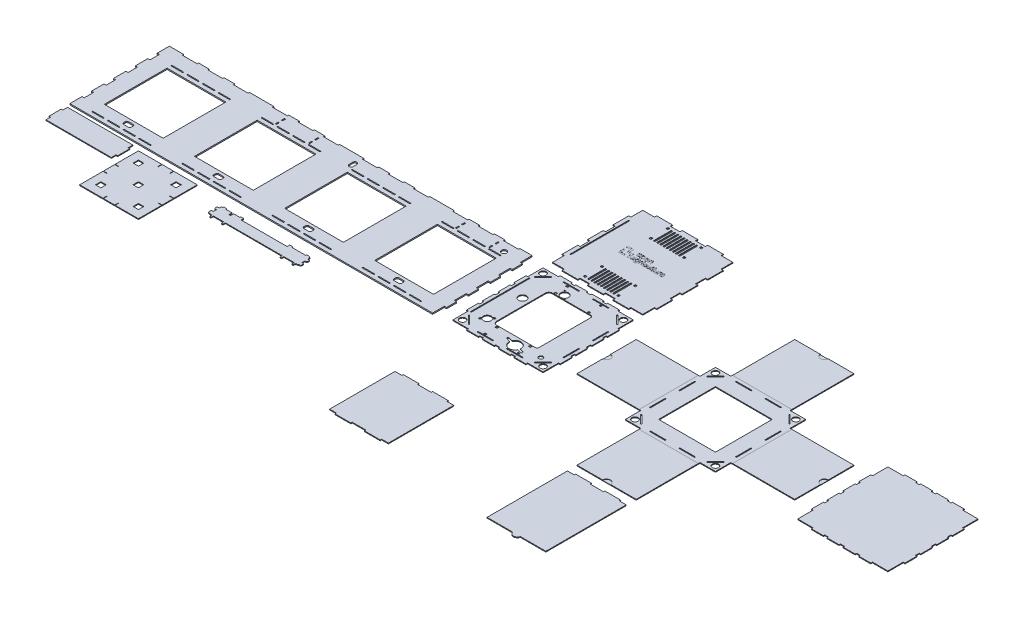
SolidWorks part; units mm, degrees
ref_plane "Front" through (0, 0, 0) normal (0, 0, 1) x (1, 0, 0)
ref_plane "Top" through (0, 0, 0) normal (0, 1, 0) x (1, 0, 0)
ref_plane "Right" through (0, 0, 0) normal (1, 0, 0) x (0, 0, -1)
sketch "Sketch1" plane through (0, 0, 0) normal (0, 1, 0) x (1, 0, 0)
  line L0 (0, 0) -> (438.15, 0) construction
  line L2 (-146.05, 161.29) -> (-146.05, -161.29) construction
  line L4 (146.05, 161.29) -> (146.05, -161.29) construction
  line L5 (-146.05, 161.29) -> (146.05, -161.29) construction
  line L6 (-146.05, -161.29) -> (146.05, 161.29) construction
  line L11 (146.05, 161.29) -> (438.15, 161.29)
  line L12 (146.05, 161.29) -> (146.05, -161.29) construction
  line L13 (146.05, -161.29) -> (438.15, -161.29)
  line L14 (438.15, 161.29) -> (438.15, -161.29) construction
  line L19 (-146.05, -161.29) -> (-438.15, -161.29)
  line L20 (-146.05, -161.29) -> (-146.05, 161.29) construction
  line L21 (-146.05, 161.29) -> (-438.15, 161.29)
  line L28 (146.05, -161.29) -> (-146.05, -161.29)
  line L34 (146.05, 161.29) -> (-146.05, 161.29)
  line L35 (-438.15, 161.29) -> (-438.15, -161.29) construction
  line L43 (-438.15, 161.29) -> (-730.25, 161.29)
  line L44 (-730.25, 161.29) -> (-730.25, -161.29) construction
  line L45 (-730.25, -161.29) -> (-438.15, -161.29)
  line L46 (438.15, 161.29) -> (438.15, 123.0884)
  line L47 (438.15, 123.0884) -> (445.262, 123.0884)
  line L48 (445.262, 123.0884) -> (445.262, 90.1954)
  line L49 (445.262, 90.1954) -> (438.15, 90.1954)
  line L50 (438.15, 90.1954) -> (438.15, 51.9938)
  line L51 (438.15, 51.9938) -> (445.262, 51.9938)
  line L63 (445.262, 51.9938) -> (445.262, 19.1008)
  line L64 (445.262, 19.1008) -> (438.15, 19.1008)
  line L65 (438.15, 19.1008) -> (438.15, -19.1008)
  line L66 (438.15, -19.1008) -> (445.262, -19.1008)
  line L67 (445.262, -19.1008) -> (445.262, -51.9938)
  line L68 (445.262, -51.9938) -> (438.15, -51.9938)
  line L69 (438.15, -51.9938) -> (438.15, -90.1954)
  line L70 (438.15, -90.1954) -> (445.262, -90.1954)
  line L71 (445.262, -90.1954) -> (445.262, -123.0884)
  line L72 (445.262, -123.0884) -> (438.15, -123.0884)
  line L73 (438.15, -123.0884) -> (438.15, -161.29)
  line L74 (-730.25, 161.29) -> (-737.362, 161.29)
  line L76 (-737.362, 121.8819) -> (-730.25, 121.8819)
  line L78 (-730.25, 91.4019) -> (-737.362, 91.4019)
  line L80 (-737.362, 50.7873) -> (-730.25, 50.7873)
  line L82 (-730.25, 20.3073) -> (-737.362, 20.3073)
  line L84 (-737.362, -20.3073) -> (-730.25, -20.3073)
  line L86 (-730.25, -50.7873) -> (-737.362, -50.7873)
  line L88 (-737.362, -91.4019) -> (-730.25, -91.4019)
  line L90 (-730.25, -121.8819) -> (-737.362, -121.8819)
  line L92 (-737.362, -161.29) -> (-730.25, -161.29)
  line L93 (445.262, 35.5473) -> (-730.25, 35.5473) construction
  line L94 (-730.25, 106.6419) -> (445.262, 106.6419) construction
  line L95 (-737.362, 161.29) -> (-737.362, 121.8819)
  line L96 (-737.362, 91.4019) -> (-737.362, 50.7873)
  line L97 (-730.25, 121.8819) -> (-730.25, 91.4019)
  line L98 (-730.25, 50.7873) -> (-730.25, 20.3073)
  line L99 (-730.25, -20.3073) -> (-730.25, -50.7873)
  line L100 (-730.25, -91.4019) -> (-730.25, -121.8819)
  line L101 (-730.25, -106.6419) -> (445.262, -106.6419) construction
  line L102 (-730.25, -35.5473) -> (445.262, -35.5473) construction
  line L103 (-737.362, 20.3073) -> (-737.362, -20.3073)
  line L104 (-737.362, -50.7873) -> (-737.362, -91.4019)
  line L105 (-737.362, -121.8819) -> (-737.362, -161.29)
  point P0 (0, 0)
  dimension "D1" = 292.1
  dimension "D2" = 322.58
  dimension "D3" = 7.112
  dimension "D4" = 32.893
  dimension "D5" = 30.48
extrude "OVERALL DIMENSIONS AND MATERIAL THICKNESS" add sketch "Sketch1" along normal blind 3.9688
sketch "Sketch4" plane through (0, 3.9688, 0) normal (0, 1, 0) x (1, 0, 0)
  line L0 (-438.15, 161.29) -> (-438.15, -161.29) construction
  line L1 (-438.15, 161.29) -> (-438.15, -161.29)
  line L2 (-146.05, 161.29) -> (-146.05, -161.29) construction
  line L3 (-146.05, 161.29) -> (-146.05, -161.29)
  line L4 (146.05, 161.29) -> (146.05, -161.29) construction
  line L5 (146.05, 161.29) -> (146.05, -161.29)
sketch "Sketch5" plane through (0, 3.9688, 0) normal (0, 1, 0) x (1, 0, 0)
  line L0 (-730.25, -20.3073) -> (-730.25, 20.3073) construction
  line L1 (-438.15, 0) -> (-730.25, 0) construction
  line L2 (-438.15, 161.29) -> (-438.15, -161.29) construction
  line L3 (-438.15, 0) -> (-146.05, 0) construction
  line L4 (-146.05, 161.29) -> (-146.05, -161.29) construction
  line L5 (-146.05, 0) -> (146.05, 0) construction
  line L6 (146.05, 161.29) -> (146.05, -161.29) construction
  line L7 (146.05, 0) -> (438.15, 0) construction
  line L8 (438.15, -19.1008) -> (438.15, 19.1008) construction
  line L9 (-584.2, -5.7594) -> (-584.2, -161.29) construction
  line L10 (-737.362, -161.29) -> (438.15, -161.29) construction
  line L11 (-292.1, -5.7594) -> (-292.1, -161.29) construction
  line L12 (0, -5.7595) -> (0, -161.29) construction
  line L13 (292.1, -5.7594) -> (292.1, -161.29) construction
  line L14 (-488.95, -148.59) -> (-488.95, -161.29) construction
  line L15 (-679.45, -145.4595) -> (-488.95, -145.4595)
  line L16 (-679.45, -145.4595) -> (-679.45, -148.59)
  line L17 (-679.45, -148.59) -> (-488.95, -148.59)
  line L18 (-488.95, -145.4595) -> (-488.95, -148.59)
  line L19 (-679.45, -145.4595) -> (-488.95, -148.59) construction
  line L20 (-679.45, -148.59) -> (-488.95, -145.4595) construction
  line L21 (-387.35, -145.4595) -> (-196.85, -145.4595)
  line L22 (-387.35, -145.4595) -> (-387.35, -148.59)
  line L23 (-387.35, -148.59) -> (-196.85, -148.59)
  line L24 (-196.85, -145.4595) -> (-196.85, -148.59)
  line L25 (-387.35, -145.4595) -> (-196.85, -148.59) construction
  line L26 (-387.35, -148.59) -> (-196.85, -145.4595) construction
  line L27 (-95.25, -148.59) -> (95.25, -148.59)
  line L28 (-95.25, -148.59) -> (-95.25, -145.4595)
  line L29 (-95.25, -145.4595) -> (95.25, -145.4595)
  line L30 (95.25, -148.59) -> (95.25, -145.4595)
  line L31 (-95.25, -148.59) -> (95.25, -145.4595) construction
  line L32 (-95.25, -145.4595) -> (95.25, -148.59) construction
  line L33 (196.85, -148.59) -> (387.35, -148.59)
  line L34 (196.85, -148.59) -> (196.85, -145.4595)
  line L35 (196.85, -145.4595) -> (387.35, -145.4595)
  line L36 (387.35, -148.59) -> (387.35, -145.4595)
  line L37 (196.85, -148.59) -> (387.35, -145.4595) construction
  line L38 (196.85, -145.4595) -> (387.35, -148.59) construction
  line L39 (445.262, 90.1954) -> (445.262, 123.0884) construction
  line L47 (-584.2, -5.7594) -> (-584.2, 110.1058) construction
  line L64 (-292.1, -5.7594) -> (-292.1, 110.1058) construction
  line L65 (-679.45, 95.8405) -> (-488.95, 95.8405)
  line L66 (-679.45, 95.8405) -> (-679.45, -107.3594)
  line L67 (-679.45, -107.3594) -> (-488.95, -107.3594)
  line L68 (-488.95, 95.8405) -> (-488.95, -107.3594)
  line L69 (-679.45, 95.8405) -> (-488.95, -107.3594) construction
  line L70 (-679.45, -107.3594) -> (-488.95, 95.8405) construction
  line L71 (-387.35, 95.8405) -> (-196.85, 95.8405)
  line L72 (-387.35, 95.8405) -> (-387.35, -107.3594)
  line L73 (-387.35, -107.3594) -> (-196.85, -107.3594)
  line L74 (-196.85, 95.8405) -> (-196.85, -107.3594)
  line L75 (-387.35, 95.8405) -> (-196.85, -107.3594) construction
  line L76 (-387.35, -107.3594) -> (-196.85, 95.8405) construction
  line L77 (-95.25, 95.8405) -> (95.25, 95.8405)
  line L78 (-95.25, 95.8405) -> (-95.25, -107.3594)
  line L79 (-95.25, -107.3594) -> (95.25, -107.3594)
  line L80 (95.25, 95.8405) -> (95.25, -107.3594)
  line L81 (-95.25, 95.8405) -> (95.25, -107.3594) construction
  line L82 (-95.25, -107.3594) -> (95.25, 95.8405) construction
  line L83 (196.85, 95.8405) -> (387.35, 95.8405)
  line L84 (196.85, 95.8405) -> (196.85, -107.3594)
  line L85 (196.85, -107.3594) -> (387.35, -107.3594)
  line L86 (387.35, 95.8405) -> (387.35, -107.3594)
  line L87 (196.85, 95.8405) -> (387.35, -107.3594) construction
  line L88 (196.85, -107.3594) -> (387.35, 95.8405) construction
  line L89 (0, -5.7595) -> (0, 110.1058) construction
  line L90 (292.1, -5.7594) -> (292.1, 110.1058) construction
  line L91 (-387.35, -107.3594) -> (-387.35, -145.4595) construction
  line L92 (-679.45, 111.6711) -> (-488.95, 111.6711)
  line L93 (-679.45, 111.6711) -> (-679.45, 108.5406)
  line L94 (-679.45, 108.5406) -> (-488.95, 108.5405)
  line L95 (-488.95, 111.6711) -> (-488.95, 108.5405)
  line L96 (-679.45, 111.6711) -> (-488.95, 108.5405) construction
  line L97 (-679.45, 108.5406) -> (-488.95, 111.6711) construction
  line L98 (-387.35, 111.6711) -> (-196.85, 111.6711)
  line L99 (-387.35, 111.6711) -> (-387.35, 108.5405)
  line L100 (-387.35, 108.5405) -> (-196.85, 108.5405)
  line L101 (-196.85, 111.6711) -> (-196.85, 108.5405)
  line L102 (-387.35, 111.6711) -> (-196.85, 108.5405) construction
  line L103 (-387.35, 108.5405) -> (-196.85, 111.6711) construction
  line L104 (-95.25, 111.6711) -> (95.25, 111.6711)
  line L105 (-95.25, 111.6711) -> (-95.25, 108.5405)
  line L106 (-95.25, 108.5405) -> (95.25, 108.5405)
  line L107 (95.25, 111.6711) -> (95.25, 108.5405)
  line L108 (-95.25, 111.6711) -> (95.25, 108.5405) construction
  line L109 (-95.25, 108.5405) -> (95.25, 111.6711) construction
  line L110 (196.85, 111.6711) -> (387.35, 111.6711)
  line L111 (196.85, 111.6711) -> (196.85, 108.5405)
  line L112 (196.85, 108.5405) -> (387.35, 108.5405)
  line L113 (387.35, 111.6711) -> (387.35, 108.5405)
  line L114 (196.85, 111.6711) -> (387.35, 108.5405) construction
  line L115 (196.85, 108.5405) -> (387.35, 111.6711) construction
  line L116 (-196.85, -107.3594) -> (-196.85, -145.4595) construction
  line L117 (-196.85, -126.4094) -> (-387.35, -126.4094) construction
  line L118 (-7.62, -132.7595) -> (7.62, -132.7595)
  line L119 (-299.72, -116.8844) -> (-284.48, -116.8844)
  line L120 (-304.8, -121.9645) -> (-304.8, -127.6794)
  line L121 (-299.72, -132.7595) -> (-284.48, -132.7595)
  line L122 (-279.4, -121.9645) -> (-279.4, -127.6794)
  line L123 (-304.8, -116.8844) -> (-279.4, -132.7595) construction
  line L124 (-304.8, -132.7595) -> (-279.4, -116.8844) construction
  line L125 (-12.7, -121.9645) -> (-12.7, -127.6794)
  line L126 (-7.62, -116.8844) -> (7.62, -116.8844)
  line L127 (12.7, -121.9645) -> (12.7, -127.6794)
  line L128 (284.48, -132.7595) -> (299.72, -132.7595)
  line L129 (279.4, -121.9645) -> (279.4, -127.6794)
  line L130 (284.48, -116.8844) -> (299.72, -116.8844)
  line L131 (304.8, -121.9645) -> (304.8, -127.6794)
  line L132 (-596.9, -121.9645) -> (-596.9, -127.6795)
  line L133 (-591.82, -116.8845) -> (-576.58, -116.8845)
  line L134 (-571.5, -121.9645) -> (-571.5, -127.6795)
  line L135 (-591.82, -132.7595) -> (-576.58, -132.7595)
  line L136 (438.15, 161.29) -> (-737.362, 161.29) construction
  line L137 (-107.95, 133.2611) -> (-107.95, 120.5611) construction
  line L138 (-101.6, 133.2611) -> (-101.6, 120.5611)
  line L139 (-114.3, 133.2611) -> (-114.3, 120.5611)
  line L142 (-107.95, 126.9111) -> (381.762, 126.9111) construction
  arc A0 (-284.48, -116.8844) -> (-279.4, -121.9645) centre (-284.48, -121.9645) cw
  arc A1 (-279.4, -127.6794) -> (-284.48, -132.7595) centre (-284.48, -127.6794) cw
  arc A2 (-299.72, -132.7595) -> (-304.8, -127.6794) centre (-299.72, -127.6794) cw
  arc A3 (-304.8, -121.9645) -> (-299.72, -116.8844) centre (-299.72, -121.9645) cw
  arc A4 (-7.62, -132.7595) -> (-12.7, -127.6794) centre (-7.62, -127.6794) cw
  arc A5 (-12.7, -121.9645) -> (-7.62, -116.8844) centre (-7.62, -121.9645) cw
  arc A6 (7.62, -116.8844) -> (12.7, -121.9645) centre (7.62, -121.9645) cw
  arc A7 (12.7, -127.6794) -> (7.62, -132.7595) centre (7.62, -127.6794) cw
  arc A8 (284.48, -132.7595) -> (279.4, -127.6794) centre (284.48, -127.6794) cw
  arc A9 (279.4, -121.9645) -> (284.48, -116.8844) centre (284.48, -121.9645) cw
  arc A10 (299.72, -116.8844) -> (304.8, -121.9645) centre (299.72, -121.9645) cw
  arc A11 (304.8, -127.6794) -> (299.72, -132.7595) centre (299.72, -127.6794) cw
  arc A12 (-596.9, -121.9645) -> (-591.82, -116.8845) centre (-591.82, -121.9645) cw
  arc A13 (-591.82, -132.7595) -> (-596.9, -127.6795) centre (-591.82, -127.6795) cw
  arc A14 (-576.58, -116.8845) -> (-571.5, -121.9645) centre (-576.58, -121.9645) cw
  arc A15 (-571.5, -127.6795) -> (-576.58, -132.7595) centre (-576.58, -127.6795) cw
  arc A16 (-101.6, 133.2611) -> (-114.3, 133.2611) centre (-107.95, 133.2611) ccw
  arc A17 (-114.3, 120.5611) -> (-101.6, 120.5611) centre (-107.95, 120.5611) ccw
  circle A18 centre (381.762, 126.9111) radius 8.255
  point P27 (-584.2, -147.0247)
  point P32 (-292.1, -147.0247)
  point P37 (0, -147.0247)
  point P42 (292.1, -147.0247)
  point P106 (-292.1, -124.8219)
  point P148 (0, -132.7595)
  point P161 (-584.2, -132.7595)
  point P165 (-107.95, 126.9111)
  point P176 (-584.2, 0)
  point P178 (-292.1, 0)
  point P179 (0, 0)
  point P180 (292.1, 0)
  dimension "D9" = 5.08
  dimension "D17" = 16.51
  dimension "D1" = 12.7
  dimension "D3" = 190.5
  dimension "D4" = 203.2
  dimension "D5" = 12.7
  dimension "D6" = 12.7
  dimension "D8" = 25.4
  dimension "D13" = 12.7
  dimension "D14" = 25.4
  dimension "D16" = 2.54
  dimension "D19" = 190.5
  dimension "D20" = 38.1
  dimension "D15" = 38.1
  dimension "D18" = 63.5
  dimension "D7" = 15.875
  dimension "D10" = 3
  dimension "D11" = 2
extrude "WINDOWS AND HORIZONTAL SLATS" cut sketch "Sketch5" against normal through all
sketch "Sketch6" plane through (0, 0, 0) normal (0, 1, 0) x (1, 0, 0)
  line L0 (0, 0) -> (635, 0) construction
  line L1 (635, 0) -> (635, 148.7964) construction
  line L2 (488.95, 146.05) -> (781.05, 146.05) construction
  line L3 (488.95, 146.05) -> (488.95, -146.05) construction
  line L4 (488.95, -146.05) -> (781.05, -146.05) construction
  line L5 (781.05, 146.05) -> (781.05, -146.05) construction
  line L6 (488.95, 146.05) -> (781.05, -146.05) construction
  line L7 (488.95, -146.05) -> (781.05, 146.05) construction
  line L8 (635, 0) -> (783.7964, 0) construction
  line L9 (635, 0) -> (635, -148.7964) construction
  line L10 (488.95, 96.139) -> (488.95, 146.05)
  line L11 (538.861, 151.5427) -> (731.139, 151.5428)
  line L12 (538.861, 151.5427) -> (538.861, 146.05)
  line L13 (538.861, 146.05) -> (731.139, 146.05) construction
  line L14 (731.139, 151.5428) -> (731.139, 146.05)
  line L15 (538.861, 151.5427) -> (731.139, 146.05) construction
  line L16 (538.861, 146.05) -> (731.139, 151.5428) construction
  line L17 (786.5428, -96.139) -> (781.05, -96.139)
  line L18 (786.5428, -96.139) -> (786.5428, 96.139)
  line L19 (786.5428, 96.139) -> (781.05, 96.139)
  line L20 (781.05, -96.139) -> (781.05, 96.139) construction
  line L21 (786.5428, -96.139) -> (781.05, 96.139) construction
  line L22 (786.5428, 96.139) -> (781.05, -96.139) construction
  line L23 (538.861, -151.5427) -> (731.139, -151.5427)
  line L24 (538.861, -151.5427) -> (538.861, -146.05)
  line L25 (538.861, -146.05) -> (731.139, -146.05) construction
  line L26 (731.139, -151.5427) -> (731.139, -146.05)
  line L27 (538.861, -151.5427) -> (731.139, -146.05) construction
  line L28 (538.861, -146.05) -> (731.139, -151.5427) construction
  line L29 (483.4572, 96.139) -> (488.95, 96.139)
  line L30 (483.4572, 96.139) -> (483.4572, -96.139)
  line L31 (483.4572, -96.139) -> (488.95, -96.139)
  line L32 (488.95, 96.139) -> (488.95, -96.139) construction
  line L33 (483.4572, 96.139) -> (488.95, -96.139) construction
  line L34 (483.4572, -96.139) -> (488.95, 96.139) construction
  line L35 (488.95, 146.05) -> (538.861, 146.05)
  line L36 (731.139, 146.05) -> (781.05, 146.05)
  line L37 (781.05, 146.05) -> (781.05, 96.139)
  line L38 (781.05, -96.139) -> (781.05, -146.05)
  line L39 (781.05, -146.05) -> (731.139, -146.05)
  line L40 (538.861, -146.05) -> (488.95, -146.05)
  line L41 (488.95, -146.05) -> (488.95, -96.139)
  line L42 (1042.2573, 96.139) -> (1042.2573, -96.139)
  line L43 (1042.2573, 96.139) -> (1047.75, 96.139)
  line L44 (1047.75, 96.139) -> (1047.75, 146.05)
  line L45 (1047.75, 146.05) -> (1097.661, 146.05)
  line L46 (1097.661, 151.5427) -> (1097.661, 146.05)
  line L47 (1097.661, 151.5427) -> (1289.939, 151.5428)
  line L48 (1289.939, 151.5428) -> (1289.939, 146.05)
  line L49 (1289.939, 146.05) -> (1339.85, 146.05)
  line L50 (1339.85, 146.05) -> (1339.85, 96.139)
  line L51 (1345.3428, 96.139) -> (1339.85, 96.139)
  line L52 (1345.3428, -96.139) -> (1345.3428, 96.139)
  line L53 (1345.3428, -96.139) -> (1339.85, -96.139)
  line L54 (1339.85, -96.139) -> (1339.85, -146.05)
  line L55 (1339.85, -146.05) -> (1289.939, -146.05)
  line L56 (1289.939, -151.5427) -> (1289.939, -146.05)
  line L57 (1097.661, -151.5427) -> (1289.939, -151.5427)
  line L58 (1097.661, -151.5427) -> (1097.661, -146.05)
  line L59 (1097.661, -146.05) -> (1047.75, -146.05)
  line L60 (1047.75, -146.05) -> (1047.75, -96.139)
  line L61 (1042.2573, -96.139) -> (1047.75, -96.139)
  line L62 (1047.75, 146.05) -> (1339.85, -146.05) construction
  line L63 (1601.0573, 96.139) -> (1601.0572, -96.139)
  line L64 (1601.0573, 96.139) -> (1606.55, 96.139)
  line L65 (1606.55, 96.139) -> (1606.55, 146.05)
  line L66 (1606.55, 146.05) -> (1656.461, 146.05)
  line L67 (1656.461, 151.5427) -> (1656.461, 146.05)
  line L68 (1656.461, 151.5427) -> (1848.739, 151.5428)
  line L69 (1848.739, 151.5428) -> (1848.739, 146.05)
  line L70 (1848.739, 146.05) -> (1898.65, 146.05)
  line L71 (1898.65, 146.05) -> (1898.65, 96.139)
  line L72 (1904.1428, 96.139) -> (1898.65, 96.139)
  line L73 (1904.1428, -96.139) -> (1904.1428, 96.139)
  line L74 (1904.1428, -96.139) -> (1898.65, -96.139)
  line L75 (1898.65, -96.139) -> (1898.65, -146.05)
  line L76 (1898.65, -146.05) -> (1848.739, -146.05)
  line L77 (1848.739, -151.5427) -> (1848.739, -146.05)
  line L78 (1656.461, -151.5427) -> (1848.739, -151.5427)
  line L79 (1656.461, -151.5427) -> (1656.461, -146.05)
  line L80 (1656.461, -146.05) -> (1606.55, -146.05)
  line L81 (1606.55, -146.05) -> (1606.55, -96.139)
  line L82 (1601.0572, -96.139) -> (1606.55, -96.139)
  line L83 (1752.6, 151.5427) -> (1752.6, -151.5427) construction
  line L84 (1101.725, 92.075) -> (1285.875, 92.075)
  line L85 (1101.725, 92.075) -> (1101.725, -92.075)
  line L86 (1101.725, -92.075) -> (1285.875, -92.075)
  line L87 (1285.875, 92.075) -> (1285.875, -92.075)
  line L88 (1101.725, 92.075) -> (1285.875, -92.075) construction
  line L89 (1101.725, -92.075) -> (1285.875, 92.075) construction
  point P22 (486.2036, 0)
  point P67 (1193.8, 0)
  dimension "D1" = 292.1
  dimension "D2" = 292.1
  dimension "D4" = 192.278
  dimension "D5" = 635
  dimension "D8" = 184.15
  dimension "D9" = 255.7145
  dimension "D7" = 558.8
  dimension "D6" = 3
extrude "HORIZONTAL PLATFORMS" add sketch "Sketch6" along normal blind 2.54 separate body
sketch "Sketch7" plane through (0, 0, 0) normal (0, 1, 0) x (1, 0, 0)
  line L0 (-679.45, 108.5406) -> (-679.45, -103.2955) construction
  line L1 (-732.1233, -173.99) -> (-520.2873, -173.99)
  line L2 (-732.1233, -173.99) -> (-732.1233, -189.23)
  line L3 (-732.1233, -243.84) -> (-520.2873, -243.84)
  line L4 (-520.2873, -173.99) -> (-520.2873, -189.23)
  line L5 (-732.1233, -173.99) -> (-520.2873, -243.84) construction
  line L6 (-732.1233, -243.84) -> (-520.2873, -173.99) construction
  line L7 (-679.45, 95.8405) -> (-679.45, -107.3594) construction
  line L8 (-679.45, -103.2955) -> (-679.45, -107.3594) construction
  line L9 (488.95, -96.139) -> (488.95, -146.05) construction
  line L10 (488.95, -146.05) -> (538.861, -146.05) construction
  line L12 (-732.1233, -189.23) -> (-737.362, -189.23)
  line L13 (502.7026, -105.3566) -> (529.6434, -132.2974) construction
  line L14 (502.7026, -105.3566) -> (500.4351, -107.6241) construction
  line L15 (500.4351, -107.6241) -> (527.3759, -134.5649) construction
  line L16 (529.6434, -132.2974) -> (527.3759, -134.5649) construction
  line L17 (502.7026, -105.3566) -> (527.3759, -134.5649) construction
  line L18 (500.4351, -107.6241) -> (529.6434, -132.2974) construction
  line L19 (-737.362, -189.23) -> (-737.362, -228.6)
  line L20 (-737.362, -228.6) -> (-732.1233, -228.6)
  line L21 (488.95, -96.139) -> (538.861, -146.05) construction
  line L22 (515.0393, -119.9607) -> (513.9055, -121.0945) construction
  line L23 (-732.1233, -228.6) -> (-732.1233, -243.84)
  line L24 (-520.2873, -189.23) -> (-515.0485, -189.23)
  line L25 (-515.0485, -189.23) -> (-515.0485, -228.6)
  line L26 (-515.0485, -228.6) -> (-520.2873, -228.6)
  line L27 (-520.2873, -228.6) -> (-520.2873, -243.84)
  line L28 (-737.362, -161.29) -> (438.15, -161.29) construction
  line L29 (-737.362, -121.8819) -> (-737.362, -161.29) construction
  point P0 (-626.2053, -208.915)
  point P14 (515.0393, -119.9607)
  dimension "D1" = 69.85
  dimension "D2" = 4.064
  dimension "D5" = 38.1
  dimension "D7" = 12.7
  dimension "D4" = 39.37
extrude "CORNER SUPPORT" add sketch "Sketch7" along normal blind 2.54 separate body
sketch "Sketch8" plane through (0, 2.54, 0) normal (0, 1, 0) x (1, 0, 0)
  line L0 (500.4351, -107.6241) -> (527.3759, -134.5649) construction
  line L1 (529.6434, -132.2974) -> (527.3759, -134.5649) construction
  line L2 (502.7026, -105.3566) -> (529.6434, -132.2974) construction
  line L3 (502.7026, -105.3566) -> (500.4351, -107.6241) construction
  line L4 (500.4351, -107.6241) -> (527.3759, -134.5649)
  line L5 (529.6434, -132.2974) -> (527.3759, -134.5649)
  line L6 (502.7026, -105.3566) -> (529.6434, -132.2974)
  line L7 (502.7026, -105.3566) -> (500.4351, -107.6241)
  line L8 (488.95, 146.05) -> (781.05, -146.05) construction
  line L9 (529.6434, 132.2974) -> (502.7026, 105.3566)
  line L10 (529.6434, 132.2974) -> (527.3759, 134.5649)
  line L11 (527.3759, 134.5649) -> (500.4351, 107.6241)
  line L12 (502.7026, 105.3566) -> (500.4351, 107.6241)
  line L13 (767.2974, 105.3566) -> (740.3566, 132.2974)
  line L14 (767.2974, 105.3566) -> (769.5649, 107.6241)
  line L15 (769.5649, 107.6241) -> (742.6241, 134.5649)
  line L16 (740.3566, 132.2974) -> (742.6241, 134.5649)
  line L17 (740.3566, -132.2974) -> (767.2974, -105.3566)
  line L18 (740.3566, -132.2974) -> (742.6241, -134.5649)
  line L19 (742.6241, -134.5649) -> (769.5649, -107.6241)
  line L20 (767.2974, -105.3566) -> (769.5649, -107.6241)
  line L21 (1047.75, -96.139) -> (1097.661, -146.05) construction
  line L22 (1059.2351, -107.6241) -> (1061.5026, -105.3566)
  line L23 (1061.5026, -105.3566) -> (1088.4434, -132.2974)
  line L24 (1088.4434, -132.2974) -> (1086.1759, -134.5649)
  line L25 (1072.7055, -121.0945) -> (1074.973, -118.827) construction
  line L26 (1059.2351, -107.6241) -> (1086.1759, -134.5649)
  line L27 (1047.75, 146.05) -> (1339.85, -146.05) construction
  line L28 (1061.5026, 105.3566) -> (1059.2351, 107.6241)
  line L29 (1086.1759, 134.5649) -> (1059.2351, 107.6241)
  line L30 (1086.1759, 134.5649) -> (1088.4434, 132.2974)
  line L31 (1088.4434, 132.2974) -> (1061.5026, 105.3566)
  line L32 (1299.1566, 132.2974) -> (1301.4241, 134.5649)
  line L33 (1328.3649, 107.6241) -> (1301.4241, 134.5649)
  line L34 (1328.3649, 107.6241) -> (1326.0974, 105.3566)
  line L35 (1326.0974, 105.3566) -> (1299.1566, 132.2974)
  line L36 (1326.0974, -105.3566) -> (1328.3649, -107.6241)
  line L37 (1301.4241, -134.5649) -> (1328.3649, -107.6241)
  line L38 (1301.4241, -134.5649) -> (1299.1566, -132.2974)
  line L39 (1299.1566, -132.2974) -> (1326.0974, -105.3566)
  circle A0 centre (635, 0) radius 20.7898 construction
  circle A1 centre (635, 0) radius 20.7898 construction
  circle A2 centre (635, 0) radius 20.7898 construction
  circle A3 centre (635, 0) radius 20.7898 construction
  circle A4 centre (1193.8, 0) radius 130.2137 construction
  circle A5 centre (1063.4654, 130.3346) radius 10
  circle A9 centre (1324.1346, 130.3346) radius 10
  circle A10 centre (1324.1346, -130.3346) radius 10
  circle A11 centre (1063.4654, -130.3346) radius 10
  circle A12 centre (504.6654, 130.3346) radius 10
  circle A13 centre (765.3346, 130.3346) radius 10
  circle A14 centre (765.3346, -130.3346) radius 10
  circle A15 centre (504.6654, -130.3346) radius 10
  point P28 (635, 0)
  point P58 (1193.8, 0)
  point P67 (1193.8, 0)
  point P76 (635, 0)
  dimension "D3" = 20
  dimension "D4" = 22.225
  dimension "D6" = 22.225
  dimension "D1" = 4
  dimension "D2" = 4
  dimension "D5" = 4
  dimension "D7" = 4
extrude "ACCESS HOLES" cut sketch "Sketch8" against normal through all
sketch "Sketch9" plane through (0, 0, 0) normal (0, 1, 0) x (1, 0, 0)
  line L0 (-737.362, -161.29) -> (438.15, -161.29) construction
  line L1 (-495.0485, -181.29) -> (-304.5485, -181.29)
  line L2 (-495.0485, -181.29) -> (-495.0485, -371.79)
  line L3 (-495.0485, -371.79) -> (-304.5485, -371.79)
  line L4 (-304.5485, -181.29) -> (-304.5485, -371.79)
  line L5 (-495.0485, -181.29) -> (-304.5485, -371.79) construction
  line L6 (-495.0485, -371.79) -> (-304.5485, -181.29) construction
  line L7 (-408.4345, -267.904) -> (-391.1625, -267.904)
  line L8 (-408.4345, -267.904) -> (-408.4345, -285.176)
  line L9 (-408.4345, -285.176) -> (-391.1625, -285.176)
  line L10 (-391.1625, -267.904) -> (-391.1625, -285.176)
  line L11 (-408.4345, -267.904) -> (-391.1625, -285.176) construction
  line L12 (-408.4345, -285.176) -> (-391.1625, -267.904) construction
  line L13 (-460.6972, -215.6413) -> (-338.8998, -215.6413) construction
  line L14 (-460.6972, -215.6413) -> (-460.6972, -337.4387) construction
  line L15 (-460.6972, -337.4387) -> (-338.8998, -337.4387) construction
  line L16 (-338.8998, -215.6413) -> (-338.8998, -337.4387) construction
  line L17 (-460.6972, -215.6413) -> (-338.8998, -337.4387) construction
  line L18 (-460.6972, -337.4387) -> (-338.8998, -215.6413) construction
  line L19 (-469.3332, -207.0053) -> (-452.0612, -207.0053)
  line L20 (-469.3332, -207.0053) -> (-469.3332, -224.2773)
  line L21 (-469.3332, -224.2773) -> (-452.0612, -224.2773)
  line L22 (-452.0612, -207.0053) -> (-452.0612, -224.2773)
  line L23 (-469.3332, -207.0053) -> (-452.0612, -224.2773) construction
  line L24 (-469.3332, -224.2773) -> (-452.0612, -207.0053) construction
  line L25 (-469.3332, -328.8027) -> (-452.0612, -328.8027)
  line L26 (-469.3332, -328.8027) -> (-469.3332, -346.0747)
  line L27 (-469.3332, -346.0747) -> (-452.0612, -346.0747)
  line L28 (-452.0612, -328.8027) -> (-452.0612, -346.0747)
  line L29 (-469.3332, -328.8027) -> (-452.0612, -346.0747) construction
  line L30 (-469.3332, -346.0747) -> (-452.0612, -328.8027) construction
  line L31 (-330.2638, -328.8027) -> (-347.5358, -328.8027)
  line L32 (-330.2638, -328.8027) -> (-330.2638, -346.0747)
  line L33 (-330.2638, -346.0747) -> (-347.5358, -346.0747)
  line L34 (-347.5358, -328.8027) -> (-347.5358, -346.0747)
  line L35 (-330.2638, -328.8027) -> (-347.5358, -346.0747) construction
  line L36 (-330.2638, -346.0747) -> (-347.5358, -328.8027) construction
  line L37 (-347.5358, -207.0053) -> (-330.2638, -207.0053)
  line L38 (-347.5358, -207.0053) -> (-347.5358, -224.2773)
  line L39 (-347.5358, -224.2773) -> (-330.2638, -224.2773)
  line L40 (-330.2638, -207.0053) -> (-330.2638, -224.2773)
  line L41 (-347.5358, -207.0053) -> (-330.2638, -224.2773) construction
  line L42 (-347.5358, -224.2773) -> (-330.2638, -207.0053) construction
  line L43 (-515.0485, -228.6) -> (-515.0485, -189.23) construction
  point P0 (-399.7985, -276.54)
  point P5 (-399.7985, -276.54)
  point P12 (-399.7985, -276.54)
  dimension "D1" = 190.5
  dimension "D2" = 190.5
  dimension "D3" = 17.272
  dimension "D4" = 17.272
  dimension "D5" = 20
  dimension "D6" = 20
  dimension "D7" = 121.7975
extrude "HORTICUBE HOUSING" add sketch "Sketch9" along normal blind 2.54 separate body
sketch "Sketch10" [suppressed] plane through (0, 3.9688, 0) normal (0, 1, 0) x (1, 0, 0)
  line L8 (-679.45, -103.2637) -> (-488.95, -103.2637)
  line L9 (-584.2, -103.2637) -> (-584.2, -107.3594) construction
  line L14 (-679.45, 95.8405) -> (-679.45, -107.3594) construction
  line L15 (-488.95, -107.3594) -> (-488.95, 95.8405) construction
  line L16 (-679.45, -107.3594) -> (-488.95, -107.3594) construction
  line L17 (-387.35, -103.2637) -> (-196.85, -103.2637)
  line L18 (-387.35, 95.8405) -> (-387.35, -107.3594) construction
  line L19 (-196.85, -107.3594) -> (-196.85, 95.8405) construction
  line L20 (-95.25, -103.2637) -> (95.25, -103.2637)
  line L21 (-95.25, 95.8405) -> (-95.25, -107.3594) construction
  line L22 (95.25, -107.3594) -> (95.25, 95.8405) construction
  line L23 (196.85, -103.2637) -> (387.35, -103.2637)
  line L24 (196.85, 95.8405) -> (196.85, -107.3594) construction
  line L25 (387.35, -107.3594) -> (387.35, 95.8405) construction
  dimension "D2" = 4.0957
sketch "Sketch11" plane through (0, 2.54, 0) normal (0, 1, 0) x (1, 0, 0)
  line L0 (488.95, 146.05) -> (781.05, -146.05) construction
  line L18 (731.139, -146.05) -> (781.05, -146.05) construction
  line L19 (781.05, -146.05) -> (781.05, -96.139) construction
  line L109 (679.0012, -124.5383) -> (690.5024, -127.62)
  line L110 (692.0801, -121.7317) -> (680.579, -118.65)
  line L111 (642.245, -108.3784) -> (630.7438, -105.2967)
  line L112 (629.1661, -111.185) -> (640.6672, -114.2667)
  line L126 (551.6771, -78.5338) -> (554.4254, -75.7854)
  line L127 (550.8333, -72.1933) -> (548.085, -74.9417)
  line L128 (529.0957, -93.9309) -> (526.3474, -96.6793)
  line L129 (529.9395, -100.2714) -> (532.6878, -97.523)
  line L130 (699.863, 90.3227) -> (574.863, 90.3227)
  line L131 (563.5613, 79.021) -> (563.5613, -78.979)
  line L132 (574.863, -90.2808) -> (699.863, -90.2808)
  line L137 (706.1648, -83.979) -> (706.1648, 84.021)
  circle A0 centre (540.385, 28.067) radius 12.6875
  circle A1 centre (600.5844, 104.3237) radius 12.6875
  circle A2 centre (612.3808, 93.3292) radius 1.7055
  circle A3 centre (588.3905, 117.3172) radius 1.7055
  arc A4 (673.6061, -130.382) -> (677.5437, -125.183) centre (660.6231, -116.4583) ccw
  arc A5 (679.6391, -117.3629) -> (643.7025, -107.7337) centre (660.6231, -116.4583) ccw
  arc A6 (641.6071, -115.5538) -> (673.6061, -130.382) centre (660.6231, -116.4583) ccw
  arc A7 (706.1648, 84.021) -> (699.863, 90.3227) centre (699.863, 84.021) ccw
  arc A8 (699.863, -90.2808) -> (706.1648, -83.979) centre (699.863, -83.979) ccw
  arc A9 (563.5613, -78.979) -> (574.863, -90.2808) centre (574.863, -78.979) ccw
  arc A10 (574.863, 90.3227) -> (563.5613, 79.021) centre (574.863, 79.021) ccw
  circle A14 centre (540.385, 28.067) radius 12.6875 construction
  circle A15 centre (600.5844, 104.3237) radius 12.6875 construction
  circle A16 centre (612.3808, 93.3292) radius 1.7055 construction
  circle A17 centre (588.3905, 117.3172) radius 1.7055 construction
  circle A24 centre (737.0572, -109.22) radius 6.7474
  arc A97 (673.6061, -130.382) -> (677.5437, -125.183) centre (660.6231, -116.4583) ccw construction
  arc A98 (679.0012, -124.5383) -> (677.5437, -125.183) centre (678.6725, -125.765) ccw
  arc A99 (690.5024, -127.62) -> (692.0801, -121.7317) centre (691.2913, -124.6758) ccw
  arc A100 (679.6391, -117.3629) -> (680.579, -118.65) centre (680.9077, -117.4233) ccw
  arc A101 (679.6391, -117.3629) -> (643.7025, -107.7337) centre (660.6231, -116.4583) ccw construction
  arc A102 (642.245, -108.3784) -> (643.7025, -107.7337) centre (642.5737, -107.1517) ccw
  arc A103 (630.7438, -105.2967) -> (629.1661, -111.185) centre (629.955, -108.2408) ccw
  arc A104 (641.6071, -115.5538) -> (640.6672, -114.2667) centre (640.3385, -115.4934) ccw
  arc A105 (641.6071, -115.5538) -> (673.6061, -130.382) centre (660.6231, -116.4583) ccw construction
  arc A120 (551.6771, -78.5338) -> (551.466, -80.0506) centre (552.5751, -79.4318) ccw
  arc A121 (554.4254, -75.7854) -> (550.8333, -72.1933) centre (552.6294, -73.9893) ccw
  arc A122 (546.5682, -75.1527) -> (548.085, -74.9417) centre (547.1869, -74.0436) ccw
  arc A123 (546.5682, -75.1527) -> (529.3068, -92.4141) centre (540.3864, -86.2323) ccw
  arc A124 (529.0957, -93.9309) -> (529.3068, -92.4141) centre (528.1977, -93.0329) ccw
  arc A125 (526.3474, -96.6793) -> (529.9395, -100.2714) centre (528.1434, -98.4753) ccw
  arc A126 (534.2046, -97.312) -> (532.6878, -97.523) centre (533.5858, -98.421) ccw
  arc A127 (534.2046, -97.312) -> (551.466, -80.0506) centre (540.3864, -86.2323) ccw
  arc A128 (706.1648, 84.021) -> (699.863, 90.3227) centre (699.863, 84.021) ccw construction
  arc A129 (574.863, 90.3227) -> (563.5613, 79.021) centre (574.863, 79.021) ccw construction
  arc A130 (563.5613, -78.979) -> (574.863, -90.2808) centre (574.863, -78.979) ccw construction
  arc A166 (699.863, -90.2808) -> (706.1648, -83.979) centre (699.863, -83.979) ccw construction
  dimension "D1" = 13.4948
  dimension "D2" = 36.83
  dimension "D3" = 43.9928
  dimension "D4" = 6.5219
extrude "Cut-Extrude4" cut sketch "Sketch11" against normal through all
sketch "Sketch12" plane through (0, 2.54, 0) normal (0, 1, 0) x (1, 0, 0)
  line L0 (483.4573, 0) -> (563.5613, 0.021) construction
  line L1 (483.4572, 96.139) -> (483.4572, -96.139) construction
  line L2 (563.5613, 79.021) -> (563.5613, -78.979) construction
  line L3 (495.7921, 95.2532) -> (495.7921, 0.0032) construction
  line L4 (494.2522, 95.2532) -> (497.332, 95.2532) construction
  line L5 (494.2522, 95.2532) -> (494.2522, -95.2468) construction
  line L6 (494.2522, -95.2468) -> (497.332, -95.2468) construction
  line L7 (497.332, 95.2532) -> (497.332, -95.2468) construction
  line L8 (494.2522, 95.2532) -> (497.332, -95.2468) construction
  line L9 (494.2522, -95.2468) -> (497.332, 95.2532) construction
  line L10 (495.7921, 0.0032) -> (495.7921, -95.2468) construction
  line L11 (488.95, 146.05) -> (781.05, -146.05) construction
  line L12 (494.2522, -22.2218) -> (497.332, -22.2218)
  line L13 (494.2522, -22.2218) -> (494.2522, -73.0218)
  line L14 (494.2522, -73.0218) -> (497.332, -73.0218)
  line L15 (497.332, -22.2218) -> (497.332, -73.0218)
  line L16 (494.2522, -22.2218) -> (497.332, -73.0218) construction
  line L17 (494.2522, -73.0218) -> (497.332, -22.2218) construction
  line L18 (494.2522, 73.0282) -> (497.332, 73.0282)
  line L19 (494.2522, 73.0282) -> (494.2522, 22.2282)
  line L20 (494.2522, 22.2282) -> (497.332, 22.2282)
  line L21 (497.332, 73.0282) -> (497.332, 22.2282)
  line L22 (494.2522, 73.0282) -> (497.332, 22.2282) construction
  line L23 (494.2522, 22.2282) -> (497.332, 73.0282) construction
  line L24 (708.0282, 140.7478) -> (657.2282, 140.7478)
  line L25 (612.7782, 140.7478) -> (612.7782, 137.668)
  line L26 (612.7782, 140.7478) -> (561.9782, 140.7478)
  line L27 (612.7782, 137.668) -> (561.9782, 137.668)
  line L28 (708.0282, 137.668) -> (657.2282, 137.668)
  line L29 (657.2282, 140.7478) -> (657.2282, 137.668)
  line L30 (708.0282, 140.7478) -> (708.0282, 137.668)
  line L31 (561.9782, 140.7478) -> (561.9782, 137.668)
  line L32 (775.7478, -73.0282) -> (775.7478, -22.2282)
  line L33 (775.7478, 22.2218) -> (772.668, 22.2218)
  line L34 (775.7478, 22.2218) -> (775.7478, 73.0218)
  line L35 (772.668, 22.2218) -> (772.668, 73.0218)
  line L36 (772.668, -73.0282) -> (772.668, -22.2282)
  line L37 (775.7478, -22.2282) -> (772.668, -22.2282)
  line L38 (775.7478, -73.0282) -> (772.668, -73.0282)
  line L39 (775.7478, 73.0218) -> (772.668, 73.0218)
  line L40 (561.9718, -140.7478) -> (612.7718, -140.7478)
  line L41 (657.2218, -140.7478) -> (657.2218, -137.668)
  line L42 (657.2218, -140.7478) -> (708.0218, -140.7478)
  line L43 (657.2218, -137.668) -> (708.0218, -137.668)
  line L44 (561.9718, -137.668) -> (612.7718, -137.668)
  line L45 (612.7718, -140.7478) -> (612.7718, -137.668)
  line L46 (561.9718, -140.7478) -> (561.9718, -137.668)
  line L47 (708.0218, -140.7478) -> (708.0218, -137.668)
  line L48 (1042.2573, 0) -> (1101.725, 0) construction
  line L49 (1042.2573, 96.139) -> (1042.2573, -96.139) construction
  line L50 (1101.725, 92.075) -> (1101.725, -92.075) construction
  line L51 (497.332, 73.0282) -> (1053.0522, 73.0282) construction
  line L52 (497.332, -22.2218) -> (1053.0522, -22.2218) construction
  line L53 (1053.0522, 73.0282) -> (1053.0522, -22.2218) construction
  line L54 (494.2522, 22.2282) -> (483.4572, 22.2282) construction
  line L55 (1053.0522, 73.0282) -> (1056.132, 73.0282)
  line L56 (1053.0522, 73.0282) -> (1053.0522, 22.2282)
  line L57 (1053.0522, 22.2282) -> (1056.132, 22.2282)
  line L58 (1056.132, 73.0282) -> (1056.132, 22.2282)
  line L59 (1053.0522, -22.2218) -> (1056.132, -22.2218)
  line L60 (1053.0522, -22.2218) -> (1053.0522, -73.0218)
  line L61 (1053.0522, -73.0218) -> (1056.132, -73.0218)
  line L62 (1056.132, -22.2218) -> (1056.132, -73.0218)
  line L63 (1053.0522, 22.2282) -> (1042.2573, 22.2282) construction
  line L64 (1047.75, 146.05) -> (1339.85, -146.05) construction
  line L65 (1266.8282, 140.7477) -> (1216.0282, 140.7477)
  line L66 (1266.8282, 140.7477) -> (1266.8282, 137.668)
  line L67 (1266.8282, 137.668) -> (1216.0282, 137.668)
  line L68 (1216.0282, 140.7477) -> (1216.0282, 137.668)
  line L69 (1171.5782, 137.668) -> (1120.7782, 137.668)
  line L70 (1171.5782, 140.7477) -> (1171.5782, 137.668)
  line L71 (1171.5782, 140.7477) -> (1120.7782, 140.7477)
  line L72 (1120.7782, 140.7477) -> (1120.7782, 137.668)
  line L73 (1334.5477, -73.0282) -> (1334.5477, -22.2282)
  line L74 (1334.5477, -73.0282) -> (1331.468, -73.0282)
  line L75 (1331.468, -73.0282) -> (1331.468, -22.2282)
  line L76 (1334.5477, -22.2282) -> (1331.468, -22.2282)
  line L77 (1331.468, 22.2218) -> (1331.468, 73.0218)
  line L78 (1334.5477, 22.2218) -> (1331.468, 22.2218)
  line L79 (1334.5477, 22.2218) -> (1334.5477, 73.0218)
  line L80 (1334.5477, 73.0218) -> (1331.468, 73.0218)
  line L81 (1120.7718, -140.7477) -> (1171.5718, -140.7477)
  line L82 (1120.7718, -140.7477) -> (1120.7718, -137.668)
  line L83 (1120.7718, -137.668) -> (1171.5718, -137.668)
  line L84 (1171.5718, -140.7477) -> (1171.5718, -137.668)
  line L85 (1216.0218, -137.668) -> (1266.8218, -137.668)
  line L86 (1216.0218, -140.7477) -> (1216.0218, -137.668)
  line L87 (1216.0218, -140.7477) -> (1266.8218, -140.7477)
  line L88 (1266.8218, -140.7477) -> (1266.8218, -137.668)
  point P6 (495.7921, 0.0032)
  point P13 (495.7921, -47.6218)
  point P19 (635, 0)
  point P21 (495.7921, 47.6282)
  point P55 (635, 0)
  point P74 (1193.8, 0)
  point P102 (1193.8, 0)
  dimension "D2" = 190.5
  dimension "D3" = 10.795
  dimension "D4" = 50.8
  dimension "D1" = 3.0798
  dimension "D6" = 4
extrude "Cut-Extrude5" cut sketch "Sketch12" against normal through all
sketch "Sketch13" plane through (0, 2.54, 0) normal (0, 1, 0) x (1, 0, 0)
  line L0 (494.2522, 22.2282) -> (497.332, -22.2218) construction
  line L1 (497.332, -73.0218) -> (497.332, -22.2218) construction
  line L2 (494.2522, 95.2532) -> (497.332, 95.2532)
  line L3 (494.2522, 95.2532) -> (494.2522, -95.2468)
  line L4 (494.2522, -95.2468) -> (497.332, -95.2468)
  line L5 (497.332, 95.2532) -> (497.332, -95.2468)
  line L6 (494.2522, 95.2532) -> (497.332, -95.2468) construction
  line L7 (494.2522, -95.2468) -> (497.332, 95.2532) construction
  point P4 (495.7921, 0.0032)
  dimension "D1" = 190.5
extrude "Cut-Extrude6" cut sketch "Sketch13" against normal through all
sketch "Sketch14" plane through (0, 0, 0) normal (0, 1, 0) x (1, 0, 0)
  line L0 (-732.1233, -243.84) -> (-520.2873, -243.84) construction
  line L1 (539.7468, -384.5878) -> (561.9718, -384.5877)
  line L2 (539.7468, -384.5878) -> (539.7468, -596.4238)
  line L3 (539.7468, -596.4238) -> (561.9718, -596.4238)
  line L4 (730.2468, -384.5877) -> (730.2468, -596.4238)
  line L5 (539.7468, -384.5878) -> (730.2468, -596.4238) construction
  line L6 (539.7468, -596.4238) -> (730.2468, -384.5877) construction
  line L7 (660.4, 469.0427) -> (692.15, 469.0427)
  line L8 (609.6, 476.1547) -> (660.4, 476.1547)
  line L9 (561.9718, -140.7478) -> (612.7718, -140.7478) construction
  line L10 (612.7718, -140.7478) -> (657.2218, -140.7478) construction
  line L11 (657.2218, -140.7478) -> (708.0218, -140.7478) construction
  line L12 (538.861, -151.5427) -> (731.139, -151.5427) construction
  line L13 (635, 322.9927) -> (635, 151.5428) construction
  line L14 (561.9718, -140.7478) -> (561.9718, -384.5877) construction
  line L15 (612.7718, -140.7478) -> (612.7718, -384.5878) construction
  line L16 (657.2218, -140.7478) -> (657.2218, -384.5878) construction
  line L17 (708.0218, -140.7478) -> (708.0218, -384.5878) construction
  line L18 (634.9968, -490.5058) -> (730.2468, -490.5058) construction
  line L19 (561.9718, -384.5877) -> (561.9718, -380.1427)
  line L20 (561.9718, -380.1427) -> (612.7718, -380.1427)
  line L21 (612.7718, -380.1427) -> (612.7718, -384.5878)
  line L22 (657.2218, -384.5878) -> (657.2218, -380.1427)
  line L23 (657.2218, -380.1427) -> (708.0218, -380.1427)
  line L24 (708.0218, -380.1427) -> (708.0218, -384.5878)
  line L25 (612.7718, -384.5878) -> (657.2218, -384.5878)
  line L26 (708.0218, -384.5878) -> (730.2468, -384.5877)
  line L27 (708.0218, -600.8688) -> (708.0218, -596.4238)
  line L28 (657.2218, -600.8688) -> (708.0218, -600.8688)
  line L29 (657.2218, -596.4238) -> (657.2218, -600.8688)
  line L30 (612.7718, -600.8688) -> (612.7718, -596.4238)
  line L31 (561.9718, -596.4238) -> (561.9718, -600.8688)
  line L32 (561.9718, -600.8688) -> (612.7718, -600.8688)
  line L33 (612.7718, -596.4238) -> (657.2218, -596.4238)
  line L34 (708.0218, -596.4238) -> (730.2468, -596.4238)
  line L35 (1193.8, -151.5427) -> (1193.8, -514.7628) construction
  line L36 (488.95, 469.0427) -> (527.05, 469.0427)
  line L37 (1098.55, -384.5877) -> (1120.7718, -384.5878)
  line L38 (1098.55, -384.5877) -> (1098.55, -644.9377)
  line L39 (1098.55, -644.9377) -> (1181.1, -644.9377)
  line L40 (1289.05, -384.5877) -> (1289.05, -644.9377)
  line L41 (1098.55, -384.5877) -> (1289.05, -644.9377) construction
  line L42 (1098.55, -644.9377) -> (1289.05, -384.5877) construction
  line L43 (1097.661, -151.5427) -> (1289.939, -151.5427) construction
  line L44 (1120.7718, -140.7477) -> (1120.7718, -384.5878) construction
  line L45 (1171.5718, -140.7477) -> (1171.5718, -384.5878) construction
  line L46 (1216.0218, -140.7477) -> (1216.0218, -384.5878) construction
  line L47 (1266.8218, -140.7477) -> (1266.8218, -384.5878) construction
  line L48 (1120.7718, -384.5878) -> (1120.7718, -380.1427)
  line L49 (1120.7718, -380.1427) -> (1171.5718, -380.1427)
  line L50 (1171.5718, -380.1427) -> (1171.5718, -384.5878)
  line L51 (1216.0218, -384.5878) -> (1216.0218, -380.1427)
  line L52 (1216.0218, -380.1427) -> (1266.8218, -380.1427)
  line L53 (1266.8218, -380.1427) -> (1266.8218, -384.5878)
  line L54 (1171.5718, -384.5878) -> (1216.0218, -384.5878)
  line L55 (1266.8218, -384.5878) -> (1289.05, -384.5877)
  line L56 (1193.8, -514.7628) -> (1193.8, -641.6467) construction
  line L57 (1206.5, -644.9377) -> (1289.05, -644.9377)
  line L58 (488.95, 469.0427) -> (488.95, 430.9427)
  line L59 (488.95, 176.9427) -> (527.05, 176.9427)
  line L60 (781.05, 469.0427) -> (781.05, 430.9427)
  line L61 (488.95, 469.0427) -> (781.05, 176.9427) construction
  line L62 (488.95, 176.9427) -> (781.05, 469.0427) construction
  line L63 (731.139, 151.5428) -> (538.861, 151.5428) construction
  line L64 (488.95, 146.05) -> (488.95, -146.05) construction
  line L65 (635, 322.9927) -> (788.162, 322.9927) construction
  line L66 (635, 243.2875) -> (635, 189.3125) construction
  line L69 (635, 322.9927) -> (635, 400.1579) construction
  line L70 (632.46, 243.2875) -> (632.46, 189.3125)
  line L75 (635, 402.6979) -> (635, 456.6729) construction
  line L76 (632.46, 402.6979) -> (632.46, 456.6729)
  line L77 (637.54, 402.6979) -> (637.54, 456.6729)
  line L78 (637.54, 243.2875) -> (637.54, 189.3125)
  line L79 (645.16, 402.6979) -> (645.16, 456.6729) construction
  line L80 (642.62, 402.6979) -> (642.62, 456.6729)
  line L81 (647.7, 402.6979) -> (647.7, 456.6729)
  line L82 (645.16, 243.2875) -> (645.16, 189.3125) construction
  line L83 (642.62, 243.2875) -> (642.62, 189.3125)
  line L84 (647.7, 243.2875) -> (647.7, 189.3125)
  line L85 (655.32, 402.6979) -> (655.32, 456.6729) construction
  line L86 (652.78, 402.6979) -> (652.78, 456.6729)
  line L87 (657.86, 402.6979) -> (657.86, 456.6729)
  line L88 (655.32, 243.2875) -> (655.32, 189.3125) construction
  line L89 (652.78, 243.2875) -> (652.78, 189.3125)
  line L90 (657.86, 243.2875) -> (657.86, 189.3125)
  line L91 (665.48, 402.6979) -> (665.48, 456.6729) construction
  line L92 (662.94, 402.6979) -> (662.94, 456.6729)
  line L93 (668.02, 402.6979) -> (668.02, 456.6729)
  line L94 (665.48, 243.2875) -> (665.48, 189.3125) construction
  line L95 (662.94, 243.2875) -> (662.94, 189.3125)
  line L96 (668.02, 243.2875) -> (668.02, 189.3125)
  line L97 (675.64, 402.6979) -> (675.64, 456.6729) construction
  line L98 (673.1, 402.6979) -> (673.1, 456.6729)
  line L99 (678.18, 402.6979) -> (678.18, 456.6729)
  line L100 (675.64, 243.2875) -> (675.64, 189.3125) construction
  line L101 (673.1, 243.2875) -> (673.1, 189.3125)
  line L102 (678.18, 243.2875) -> (678.18, 189.3125)
  line L103 (624.84, 402.6979) -> (624.84, 456.6729) construction
  line L104 (622.3, 402.6979) -> (622.3, 456.6729)
  line L105 (627.38, 402.6979) -> (627.38, 456.6729)
  line L106 (624.84, 243.2875) -> (624.84, 189.3125) construction
  line L107 (622.3, 243.2875) -> (622.3, 189.3125)
  line L108 (627.38, 243.2875) -> (627.38, 189.3125)
  line L109 (614.68, 402.6979) -> (614.68, 456.6729) construction
  line L110 (612.14, 402.6979) -> (612.14, 456.6729)
  line L111 (617.22, 402.6979) -> (617.22, 456.6729)
  line L112 (614.68, 243.2875) -> (614.68, 189.3125) construction
  line L113 (612.14, 243.2875) -> (612.14, 189.3125)
  line L114 (617.22, 243.2875) -> (617.22, 189.3125)
  line L115 (604.52, 402.6979) -> (604.52, 456.6729) construction
  line L116 (601.98, 402.6979) -> (601.98, 456.6729)
  line L117 (607.06, 402.6979) -> (607.06, 456.6729)
  line L118 (604.52, 243.2875) -> (604.52, 189.3125) construction
  line L119 (601.98, 243.2875) -> (601.98, 189.3125)
  line L120 (607.06, 243.2875) -> (607.06, 189.3125)
  line L121 (594.36, 402.6979) -> (594.36, 456.6729) construction
  line L122 (591.82, 402.6979) -> (591.82, 456.6729)
  line L123 (596.9, 402.6979) -> (596.9, 456.6729)
  line L124 (594.36, 243.2875) -> (594.36, 189.3125) construction
  line L125 (591.82, 243.2875) -> (591.82, 189.3125)
  line L126 (596.9, 243.2875) -> (596.9, 189.3125)
  line L127 (635, 322.9927) -> (488.95, 322.9927) construction
  line L128 (494.2522, 95.2532) -> (494.2522, -95.2468) construction
  line L129 (494.2523, 418.2427) -> (497.332, 418.2427)
  line L130 (494.2523, 418.2427) -> (494.2523, 227.7427)
  line L131 (494.2523, 227.7427) -> (497.332, 227.7427)
  line L132 (497.332, 418.2427) -> (497.332, 227.7427)
  line L133 (494.2523, 418.2427) -> (497.332, 227.7427) construction
  line L134 (494.2523, 227.7427) -> (497.332, 418.2427) construction
  line L135 (497.332, 95.2532) -> (494.2522, 95.2532) construction
  line L136 (488.95, 380.1427) -> (481.838, 380.1427)
  line L137 (481.838, 380.1427) -> (481.838, 430.9427)
  line L138 (481.838, 430.9427) -> (488.95, 430.9427)
  line L139 (488.95, 215.0427) -> (481.838, 215.0427)
  line L140 (481.838, 215.0427) -> (481.838, 265.8427)
  line L141 (481.838, 265.8427) -> (488.95, 265.8427)
  line L142 (481.838, 430.9427) -> (481.838, 215.0427) construction
  line L143 (481.838, 322.9927) -> (488.95, 322.9927) construction
  line L144 (488.95, 380.1427) -> (488.95, 348.3927)
  line L145 (488.95, 215.0427) -> (488.95, 176.9427)
  line L146 (781.05, 215.0427) -> (788.162, 215.0427)
  line L147 (788.162, 215.0427) -> (788.162, 265.8427)
  line L148 (788.162, 265.8427) -> (781.05, 265.8427)
  line L149 (781.05, 380.1427) -> (788.162, 380.1427)
  line L150 (788.162, 380.1427) -> (788.162, 430.9427)
  line L151 (788.162, 430.9427) -> (781.05, 430.9427)
  line L152 (781.05, 380.1427) -> (781.05, 348.3927)
  line L153 (781.05, 215.0427) -> (781.05, 176.9427)
  line L154 (635, 469.0427) -> (635, 476.1547) construction
  line L155 (577.85, 476.1547) -> (692.15, 476.1547) construction
  line L156 (577.85, 469.0427) -> (609.6, 469.0427)
  line L158 (527.05, 469.0427) -> (527.05, 476.1547)
  line L159 (527.05, 476.1547) -> (577.85, 476.1547)
  line L160 (577.85, 469.0427) -> (577.85, 476.1547)
  line L161 (692.15, 476.1547) -> (742.95, 476.1547)
  line L162 (692.15, 476.1547) -> (692.15, 469.0427)
  line L164 (742.95, 476.1547) -> (742.95, 469.0427)
  line L165 (742.95, 469.0427) -> (781.05, 469.0427)
  line L166 (742.95, 169.8307) -> (742.95, 176.9427)
  line L167 (692.15, 169.8307) -> (742.95, 169.8307)
  line L168 (692.15, 169.8307) -> (692.15, 176.9428)
  line L169 (577.85, 176.9428) -> (577.85, 169.8307)
  line L170 (527.05, 169.8307) -> (577.85, 169.8307)
  line L171 (527.05, 176.9427) -> (527.05, 169.8307)
  line L172 (577.85, 176.9428) -> (609.6, 176.9427)
  line L173 (742.95, 176.9427) -> (781.05, 176.9427)
  line L174 (609.6, 476.1547) -> (609.6, 469.0427)
  line L176 (660.4, 476.1547) -> (660.4, 469.0427)
  line L177 (609.6, 476.1547) -> (660.4, 469.0427) construction
  line L178 (609.6, 469.0427) -> (660.4, 476.1547) construction
  line L179 (488.95, 297.5927) -> (488.95, 265.8427)
  line L180 (488.95, 348.3927) -> (481.838, 348.3927)
  line L182 (488.95, 297.5927) -> (481.838, 297.5927)
  line L183 (481.838, 348.3927) -> (481.838, 297.5927)
  line L184 (488.95, 348.3927) -> (481.838, 297.5927) construction
  line L185 (488.95, 297.5927) -> (481.838, 348.3927) construction
  line L186 (609.6, 169.8307) -> (660.4, 169.8307)
  line L187 (609.6, 169.8307) -> (609.6, 176.9427)
  line L189 (660.4, 169.8307) -> (660.4, 176.9427)
  line L190 (609.6, 169.8307) -> (660.4, 176.9427) construction
  line L191 (609.6, 176.9427) -> (660.4, 169.8307) construction
  line L192 (788.162, 297.5927) -> (781.05, 297.5927)
  line L193 (788.162, 297.5927) -> (788.162, 348.3927)
  line L194 (788.162, 348.3927) -> (781.05, 348.3927)
  line L196 (788.162, 297.5927) -> (781.05, 348.3927) construction
  line L197 (788.162, 348.3927) -> (781.05, 297.5927) construction
  line L198 (660.4, 176.9427) -> (692.15, 176.9428)
  line L199 (781.05, 297.5927) -> (781.05, 265.8427)
  line L200 (481.838, 405.5427) -> (494.2523, 405.5427) construction
  line L201 (497.332, -95.2468) -> (497.332, 95.2532) construction
  arc A0 (1181.1, -644.9377) -> (1206.5, -644.9377) centre (1193.8, -641.6467) ccw
  arc A7 (632.46, 402.6979) -> (637.54, 402.6979) centre (635, 402.6979) ccw
  arc A8 (637.54, 456.6729) -> (632.46, 456.6729) centre (635, 456.6729) ccw
  arc A9 (632.46, 243.2875) -> (637.54, 243.2875) centre (635, 243.2875) cw
  arc A10 (637.54, 189.3125) -> (632.46, 189.3125) centre (635, 189.3125) cw
  arc A11 (642.62, 402.6979) -> (647.7, 402.6979) centre (645.16, 402.6979) ccw
  arc A12 (647.7, 456.6729) -> (642.62, 456.6729) centre (645.16, 456.6729) ccw
  arc A13 (642.62, 243.2875) -> (647.7, 243.2875) centre (645.16, 243.2875) cw
  arc A14 (647.7, 189.3125) -> (642.62, 189.3125) centre (645.16, 189.3125) cw
  arc A15 (652.78, 402.6979) -> (657.86, 402.6979) centre (655.32, 402.6979) ccw
  arc A16 (657.86, 456.6729) -> (652.78, 456.6729) centre (655.32, 456.6729) ccw
  arc A17 (652.78, 243.2875) -> (657.86, 243.2875) centre (655.32, 243.2875) cw
  arc A18 (657.86, 189.3125) -> (652.78, 189.3125) centre (655.32, 189.3125) cw
  arc A19 (662.94, 402.6979) -> (668.02, 402.6979) centre (665.48, 402.6979) ccw
  arc A20 (668.02, 456.6729) -> (662.94, 456.6729) centre (665.48, 456.6729) ccw
  arc A21 (662.94, 243.2875) -> (668.02, 243.2875) centre (665.48, 243.2875) cw
  arc A22 (668.02, 189.3125) -> (662.94, 189.3125) centre (665.48, 189.3125) cw
  arc A23 (673.1, 402.6979) -> (678.18, 402.6979) centre (675.64, 402.6979) ccw
  arc A24 (678.18, 456.6729) -> (673.1, 456.6729) centre (675.64, 456.6729) ccw
  arc A25 (673.1, 243.2875) -> (678.18, 243.2875) centre (675.64, 243.2875) cw
  arc A26 (678.18, 189.3125) -> (673.1, 189.3125) centre (675.64, 189.3125) cw
  arc A27 (622.3, 402.6979) -> (627.38, 402.6979) centre (624.84, 402.6979) ccw
  arc A28 (627.38, 456.6729) -> (622.3, 456.6729) centre (624.84, 456.6729) ccw
  arc A29 (622.3, 243.2875) -> (627.38, 243.2875) centre (624.84, 243.2875) cw
  arc A30 (627.38, 189.3125) -> (622.3, 189.3125) centre (624.84, 189.3125) cw
  arc A31 (612.14, 402.6979) -> (617.22, 402.6979) centre (614.68, 402.6979) ccw
  arc A32 (617.22, 456.6729) -> (612.14, 456.6729) centre (614.68, 456.6729) ccw
  arc A33 (612.14, 243.2875) -> (617.22, 243.2875) centre (614.68, 243.2875) cw
  arc A34 (617.22, 189.3125) -> (612.14, 189.3125) centre (614.68, 189.3125) cw
  arc A35 (601.98, 402.6979) -> (607.06, 402.6979) centre (604.52, 402.6979) ccw
  arc A36 (607.06, 456.6729) -> (601.98, 456.6729) centre (604.52, 456.6729) ccw
  arc A37 (601.98, 243.2875) -> (607.06, 243.2875) centre (604.52, 243.2875) cw
  arc A38 (607.06, 189.3125) -> (601.98, 189.3125) centre (604.52, 189.3125) cw
  arc A39 (591.82, 402.6979) -> (596.9, 402.6979) centre (594.36, 402.6979) ccw
  arc A40 (596.9, 456.6729) -> (591.82, 456.6729) centre (594.36, 456.6729) ccw
  arc A41 (591.82, 243.2875) -> (596.9, 243.2875) centre (594.36, 243.2875) cw
  arc A42 (596.9, 189.3125) -> (591.82, 189.3125) centre (594.36, 189.3125) cw
  point P0 (634.9968, -490.5058)
  point P7 (635, 173.3867)
  point P8 (635, 472.5987)
  point P23 (1193.8, -514.7628)
  point P83 (635, 216.3)
  point P89 (495.7921, 322.9927)
  point P93 (645.16, 216.3)
  point P99 (635, 429.6854)
  point P107 (645.16, 429.6854)
  point P114 (655.32, 216.3)
  point P121 (655.32, 429.6854)
  point P128 (665.48, 216.3)
  point P135 (665.48, 429.6854)
  point P142 (675.64, 216.3)
  point P149 (675.64, 429.6854)
  point P155 (624.84, 216.3)
  point P162 (624.84, 429.6854)
  point P169 (614.68, 216.3)
  point P176 (614.68, 429.6854)
  point P183 (604.52, 216.3)
  point P190 (604.52, 429.6854)
  point P197 (594.36, 216.3)
  point P204 (594.36, 429.6854)
  point P256 (485.394, 322.9927)
  point P265 (784.606, 322.9927)
  point P270 (0, 0)
  dimension "D9" = 77.1652
  dimension "D12" = 2.54
  dimension "D1" = 190.5
  dimension "D2" = 228.6
  dimension "D3" = 4.445
  dimension "D4" = 190.5
  dimension "D5" = 260.35
  dimension "D6" = 25.4
  dimension "D7" = 3.291
  dimension "D8" = 25.4
  dimension "D10" = 5
  dimension "D11" = 10.16
  dimension "D13" = 53.975
  dimension "D14" = 5
  dimension "D15" = 10.16
  dimension "D16" = 7.112
  dimension "D17" = 12.7
  dimension "D18" = 50.8
  dimension "D19" = 292.1
  dimension "D20" = 292.1
  dimension "D21" = 82.55
extrude "Boss-Extrude5" add sketch "Sketch14" along normal blind 2.54 separate body
sketch "Sketch15" plane through (0, 3.9688, 0) normal (0, 1, 0) x (1, 0, 0)
  line L0 (292.1, 111.6711) -> (292.1, 161.29) construction
  line L1 (387.35, 111.6711) -> (196.85, 111.6711) construction
  line L2 (438.15, 161.29) -> (-737.362, 161.29) construction
  line L3 (233.7435, 156.845) -> (292.1, 156.845) construction
  line L4 (185.3565, 161.29) -> (233.7435, 161.29)
  line L5 (185.3565, 161.29) -> (185.3565, 156.845)
  line L6 (185.3565, 156.845) -> (233.7435, 156.845)
  line L7 (233.7435, 161.29) -> (233.7435, 156.845)
  line L8 (350.4565, 161.29) -> (398.8435, 161.29)
  line L9 (350.4565, 161.29) -> (350.4565, 156.845)
  line L10 (350.4565, 156.845) -> (398.8435, 156.845)
  line L11 (398.8435, 161.29) -> (398.8435, 156.845)
  line L12 (292.1, 156.845) -> (350.4565, 156.845) construction
  line L13 (233.7435, 161.29) -> (350.4565, 161.29) construction
  line L14 (0, 111.6711) -> (0, 161.29) construction
  line L15 (95.25, 111.6711) -> (-95.25, 111.6711) construction
  line L16 (-106.7435, 161.29) -> (-106.7435, 156.845)
  line L17 (-106.7435, 156.845) -> (-58.3565, 156.845)
  line L18 (-58.3565, 161.29) -> (-58.3565, 156.845)
  line L19 (-106.7435, 161.29) -> (-58.3565, 161.29)
  line L20 (58.3565, 161.29) -> (58.3565, 156.845)
  line L21 (58.3565, 156.845) -> (106.7435, 156.845)
  line L22 (106.7435, 161.29) -> (106.7435, 156.845)
  line L23 (58.3565, 161.29) -> (106.7435, 161.29)
  line L24 (-398.8435, 161.29) -> (-398.8435, 156.845)
  line L25 (-398.8435, 156.845) -> (-350.4565, 156.845)
  line L26 (-350.4565, 161.29) -> (-350.4565, 156.845)
  line L27 (-398.8435, 161.29) -> (-350.4565, 161.29)
  line L28 (-233.7435, 161.29) -> (-233.7435, 156.845)
  line L29 (-233.7435, 156.845) -> (-185.3565, 156.845)
  line L30 (-185.3565, 161.29) -> (-185.3565, 156.845)
  line L31 (-233.7435, 161.29) -> (-185.3565, 161.29)
  line L32 (-690.9435, 161.29) -> (-690.9435, 156.845)
  line L33 (-690.9435, 156.845) -> (-642.5565, 156.845)
  line L34 (-642.5565, 161.29) -> (-642.5565, 156.845)
  line L35 (-690.9435, 161.29) -> (-642.5565, 161.29)
  line L36 (-525.8435, 161.29) -> (-525.8435, 156.845)
  line L37 (-525.8435, 156.845) -> (-477.4565, 156.845)
  line L38 (-477.4565, 161.29) -> (-477.4565, 156.845)
  line L39 (-525.8435, 161.29) -> (-477.4565, 161.29)
  line L40 (-292.1, 111.6711) -> (-292.1, 161.29) construction
  line L41 (267.9065, 161.29) -> (316.2935, 161.29)
  line L42 (267.9065, 161.29) -> (267.9065, 156.845)
  line L43 (267.9065, 156.845) -> (316.2935, 156.845)
  line L44 (316.2935, 161.29) -> (316.2935, 156.845)
  line L45 (267.9065, 161.29) -> (316.2935, 156.845) construction
  line L46 (267.9065, 156.845) -> (316.2935, 161.29) construction
  line L47 (-24.1935, 161.29) -> (24.1935, 161.29)
  line L48 (-24.1935, 161.29) -> (-24.1935, 156.845)
  line L49 (-24.1935, 156.845) -> (24.1935, 156.845)
  line L50 (24.1935, 161.29) -> (24.1935, 156.845)
  line L51 (-24.1935, 161.29) -> (24.1935, 156.845) construction
  line L52 (-24.1935, 156.845) -> (24.1935, 161.29) construction
  line L53 (-196.85, 111.6711) -> (-387.35, 111.6711) construction
  line L54 (-584.2, 111.6711) -> (-584.2, 161.29) construction
  line L55 (-488.95, 111.6711) -> (-679.45, 111.6711) construction
  line L56 (209.55, 156.845) -> (209.55, 161.29) construction
  line L57 (-608.3935, 161.29) -> (-560.0065, 161.29)
  line L58 (-608.3935, 161.29) -> (-608.3935, 156.845)
  line L59 (-608.3935, 156.845) -> (-560.0065, 156.845)
  line L60 (-560.0065, 161.29) -> (-560.0065, 156.845)
  line L61 (-608.3935, 161.29) -> (-560.0065, 156.845) construction
  line L62 (-608.3935, 156.845) -> (-560.0065, 161.29) construction
  line L63 (-316.2935, 161.29) -> (-267.9065, 161.29)
  line L64 (-316.2935, 161.29) -> (-316.2935, 156.845)
  line L65 (-316.2935, 156.845) -> (-267.9065, 156.845)
  line L66 (-267.9065, 161.29) -> (-267.9065, 156.845)
  line L67 (-316.2935, 161.29) -> (-267.9065, 156.845) construction
  line L68 (-316.2935, 156.845) -> (-267.9065, 161.29) construction
  point P21 (292.1, 159.0675)
  point P49 (0, 159.0675)
  point P62 (-584.2, 159.0675)
  point P67 (-292.1, 159.0675)
  dimension "D1" = 48.387
  dimension "D2" = 4.445
  dimension "D3" = 82.55
  dimension "D4" = 4
  dimension "D5" = 292.1
extrude "Cut-Extrude7" cut sketch "Sketch15" against normal through all
sketch "Sketch16" plane through (0, 3.9688, 0) normal (0, 1, 0) x (1, 0, 0)
  line L0 (-584.2, 111.6711) -> (-584.2, 108.5405) construction
  line L1 (-488.95, 111.6711) -> (-679.45, 111.6711) construction
  line L2 (-679.45, 108.5406) -> (-488.95, 108.5405) construction
  line L3 (-488.95, 108.5405) -> (-488.95, 111.6711) construction
  line L4 (-590.55, 111.6711) -> (-577.85, 111.6711)
  line L5 (-590.55, 111.6711) -> (-590.55, 108.5405)
  line L6 (-590.55, 108.5405) -> (-577.85, 108.5405)
  line L7 (-577.85, 111.6711) -> (-577.85, 108.5405)
  line L8 (-590.55, 111.6711) -> (-577.85, 108.5405) construction
  line L9 (-590.55, 108.5405) -> (-577.85, 111.6711) construction
  line L10 (-584.2, -145.4595) -> (-584.2, -148.59) construction
  line L11 (-488.95, -145.4595) -> (-679.45, -145.4595) construction
  line L12 (-679.45, -148.59) -> (-488.95, -148.59) construction
  line L13 (-298.45, 111.6711) -> (-285.75, 111.6711)
  line L14 (-590.55, -145.4595) -> (-577.85, -145.4595)
  line L15 (-590.55, -145.4595) -> (-590.55, -148.59)
  line L16 (-590.55, -148.59) -> (-577.85, -148.59)
  line L17 (-577.85, -145.4595) -> (-577.85, -148.59)
  line L18 (-590.55, -145.4595) -> (-577.85, -148.59) construction
  line L19 (-590.55, -148.59) -> (-577.85, -145.4595) construction
  line L20 (-298.45, 111.6711) -> (-298.45, 108.5405)
  line L21 (-298.45, 108.5405) -> (-285.75, 108.5405)
  line L22 (-285.75, 111.6711) -> (-285.75, 108.5405)
  line L23 (-285.75, -145.4595) -> (-285.75, -148.59)
  line L24 (-298.45, -148.59) -> (-285.75, -148.59)
  line L25 (-298.45, -145.4595) -> (-298.45, -148.59)
  line L26 (-298.45, -145.4595) -> (-285.75, -145.4595)
  line L27 (-6.35, 111.6711) -> (6.35, 111.6711)
  line L28 (-6.35, 111.6711) -> (-6.35, 108.5405)
  line L29 (-6.35, 108.5405) -> (6.35, 108.5405)
  line L30 (6.35, 111.6711) -> (6.35, 108.5405)
  line L31 (6.35, -145.4595) -> (6.35, -148.59)
  line L32 (-6.35, -148.59) -> (6.35, -148.59)
  line L33 (-6.35, -145.4595) -> (-6.35, -148.59)
  line L34 (-6.35, -145.4595) -> (6.35, -145.4595)
  line L35 (285.75, 111.6711) -> (298.45, 111.6711)
  line L36 (285.75, 111.6711) -> (285.75, 108.5405)
  line L37 (285.75, 108.5405) -> (298.45, 108.5405)
  line L38 (298.45, 111.6711) -> (298.45, 108.5405)
  line L39 (298.45, -145.4595) -> (298.45, -148.59)
  line L40 (285.75, -148.59) -> (298.45, -148.59)
  line L41 (285.75, -145.4595) -> (285.75, -148.59)
  line L42 (285.75, -145.4595) -> (298.45, -145.4595)
  point P6 (-584.2, 110.1058)
  point P19 (-584.2, -147.0247)
  dimension "D1" = 88.9
  dimension "D3" = 292.1
  dimension "D2" = 4
extrude "Boss-Extrude6" add sketch "Sketch16" against normal up to surface (3.9688 mm away) up to face at (-146.2193, 0, -90.8957)
sketch "Sketch17" plane through (0, 2.54, 0) normal (0, 1, 0) x (1, 0, 0)
  line L0 (635, 151.5428) -> (635, -151.5427) construction
  line L1 (731.139, 151.5428) -> (538.861, 151.5427) construction
  line L2 (538.861, -151.5427) -> (731.139, -151.5427) construction
  line L3 (298.45, 111.6711) -> (285.75, 111.6711) construction
  line L4 (628.3325, 147.0978) -> (641.6675, 147.0978)
  line L5 (628.3325, 147.0978) -> (628.3325, 151.5428)
  line L6 (628.3325, 151.5428) -> (641.6675, 151.5428)
  line L7 (641.6675, 147.0978) -> (641.6675, 151.5428)
  line L8 (628.3325, 147.0978) -> (641.6675, 151.5428) construction
  line L9 (628.3325, 151.5428) -> (641.6675, 147.0978) construction
  line L10 (483.4573, 0) -> (786.5428, 0) construction
  line L11 (628.3325, -147.0977) -> (641.6675, -147.0977)
  line L12 (628.3325, -147.0977) -> (628.3325, -151.5427)
  line L13 (628.3325, -151.5427) -> (641.6675, -151.5427)
  line L14 (641.6675, -147.0977) -> (641.6675, -151.5427)
  line L15 (628.3325, -147.0977) -> (641.6675, -151.5427) construction
  line L16 (628.3325, -151.5427) -> (641.6675, -147.0977) construction
  line L17 (483.4572, 96.139) -> (483.4572, -96.139) construction
  line L18 (786.5428, -96.139) -> (786.5428, 96.139) construction
  line L19 (1046.7023, 6.6675) -> (1046.7023, -6.6675) construction
  line L20 (487.9023, 6.6675) -> (483.4573, 6.6675)
  line L21 (487.9023, 6.6675) -> (487.9023, -6.6675)
  line L22 (487.9023, -6.6675) -> (483.4573, -6.6675)
  line L23 (483.4573, 6.6675) -> (483.4573, -6.6675)
  line L24 (487.9023, 6.6675) -> (483.4573, -6.6675) construction
  line L25 (487.9023, -6.6675) -> (483.4573, 6.6675) construction
  line L26 (782.0978, -6.6675) -> (786.5428, -6.6675)
  line L27 (782.0978, -6.6675) -> (782.0978, 6.6675)
  line L28 (782.0978, 6.6675) -> (786.5428, 6.6675)
  line L29 (786.5428, -6.6675) -> (786.5428, 6.6675)
  line L30 (782.0978, -6.6675) -> (786.5428, 6.6675) construction
  line L31 (782.0978, 6.6675) -> (786.5428, -6.6675) construction
  line L32 (1046.7023, 6.6675) -> (1042.2573, 6.6675) construction
  line L33 (1042.2573, 6.6675) -> (1042.2573, -6.6675) construction
  line L34 (1046.7023, -6.6675) -> (1042.2573, -6.6675) construction
  line L35 (1187.1325, -147.0977) -> (1187.1325, -151.5427) construction
  line L36 (1187.1325, -147.0977) -> (1200.4675, -147.0977) construction
  line L37 (1200.4675, -147.0977) -> (1200.4675, -151.5427) construction
  line L38 (1187.1325, -151.5427) -> (1200.4675, -151.5427) construction
  line L39 (1340.8978, -6.6675) -> (1340.8978, 6.6675) construction
  line L40 (1340.8978, -6.6675) -> (1345.3428, -6.6675) construction
  line L41 (1345.3428, -6.6675) -> (1345.3428, 6.6675) construction
  line L42 (1340.8978, 6.6675) -> (1345.3428, 6.6675) construction
  line L43 (1187.1325, 147.0978) -> (1187.1325, 151.5428) construction
  line L44 (1187.1325, 147.0978) -> (1200.4675, 147.0978) construction
  line L45 (1200.4675, 147.0978) -> (1200.4675, 151.5428) construction
  line L46 (1187.1325, 151.5428) -> (1200.4675, 151.5428) construction
  line L47 (1605.5023, 6.6675) -> (1605.5023, -6.6675)
  line L48 (1605.5023, 6.6675) -> (1601.0573, 6.6675)
  line L49 (1601.0573, 6.6675) -> (1601.0573, -6.6675)
  line L50 (1605.5023, -6.6675) -> (1601.0573, -6.6675)
  line L51 (1745.9325, -147.0977) -> (1745.9325, -151.5427)
  line L52 (1745.9325, -147.0977) -> (1759.2675, -147.0977)
  line L53 (1759.2675, -147.0977) -> (1759.2675, -151.5427)
  line L54 (1745.9325, -151.5427) -> (1759.2675, -151.5427)
  line L55 (1899.6978, -6.6675) -> (1899.6978, 6.6675)
  line L56 (1899.6978, -6.6675) -> (1904.1428, -6.6675)
  line L57 (1904.1428, -6.6675) -> (1904.1428, 6.6675)
  line L58 (1899.6978, 6.6675) -> (1904.1428, 6.6675)
  line L59 (1745.9325, 147.0978) -> (1745.9325, 151.5428)
  line L60 (1745.9325, 147.0978) -> (1759.2675, 147.0978)
  line L61 (1759.2675, 147.0978) -> (1759.2675, 151.5428)
  line L62 (1745.9325, 151.5428) -> (1759.2675, 151.5428)
  line L63 (1289.939, 151.5428) -> (1097.661, 151.5427) construction
  point P6 (635, 149.3203)
  point P15 (635, -149.3202)
  point P25 (784.3203, 0)
  point P28 (485.6798, 0)
  dimension "D1" = 12.7
  dimension "D2" = 13.335
  dimension "D3" = 4.445
  dimension "D5" = 558.8
  dimension "D4" = 3
extrude "Cut-Extrude8" cut sketch "Sketch17" against normal through all
sketch "Sketch19" plane through (0, 0, 0) normal (0, 1, 0) x (1, 0, 0)
  line L0 (74.4574, -250.4153) -> (75.2512, -249.6215)
  line L1 (70.9237, -249.6215) -> (71.7175, -250.4153)
  line L2 (36.435, -250.4153) -> (37.2287, -249.6215)
  line L3 (32.2287, -249.6215) -> (33.0225, -250.4153)
  line L4 (-153.075, -250.4153) -> (-152.2813, -249.6215)
  line L5 (-157.2813, -249.6215) -> (-156.4875, -250.4153)
  line L6 (-191.77, -250.4153) -> (-190.9763, -249.6215)
  line L7 (-195.2055, -249.6215) -> (-194.4118, -250.4153)
  line L8 (-210.0263, -238.8278) -> (-208.4388, -240.4153)
  line L9 (-208.4388, -230.4153) -> (-210.0263, -232.0028)
  line L10 (-210.0263, -218.8278) -> (-208.4388, -220.4153)
  line L11 (-208.4388, -210.4153) -> (-210.0263, -212.0028)
  line L12 (-198.3575, -200.4153) -> (-199.1513, -201.209)
  line L13 (-189.1513, -201.209) -> (-189.945, -200.4153)
  line L14 (-143.4935, -200.4153) -> (-144.2873, -201.209)
  line L15 (-134.2873, -201.209) -> (-135.081, -200.4153)
  line L16 (-133.1647, -208.9625) -> (13.1122, -208.9625)
  line L17 (15.0285, -200.4153) -> (14.2347, -201.209)
  line L18 (24.2347, -201.209) -> (23.441, -200.4153)
  line L19 (69.8925, -200.4153) -> (69.0987, -201.209)
  line L20 (79.0987, -201.209) -> (78.305, -200.4153)
  line L21 (89.9737, -212.0028) -> (88.3862, -210.4153)
  line L22 (88.3862, -220.4153) -> (89.9737, -218.8278)
  line L23 (89.9737, -232.0028) -> (88.3862, -230.4153)
  line L24 (88.3862, -240.4153) -> (89.9737, -238.8278)
  line L25 (38.3513, -242.4905) -> (69.8012, -242.4905)
  line L26 (37.2287, -249.6215) -> (37.2287, -243.613)
  line L27 (33.0225, -250.4153) -> (36.435, -250.4153)
  line L28 (32.2287, -243.613) -> (32.2287, -249.6215)
  line L29 (-151.1587, -242.4905) -> (31.1062, -242.4905)
  line L30 (-152.2813, -249.6215) -> (-152.2813, -243.613)
  line L31 (-156.4875, -250.4153) -> (-153.075, -250.4153)
  line L32 (-157.2813, -243.613) -> (-157.2813, -249.6215)
  line L33 (-189.8537, -242.4905) -> (-158.4038, -242.4905)
  line L34 (-190.9763, -249.6215) -> (-190.9763, -243.613)
  line L35 (-194.4118, -250.4153) -> (-191.77, -250.4153)
  line L36 (-195.2055, -245.1878) -> (-195.2055, -249.6215)
  line L37 (-197.3263, -244.0653) -> (-196.328, -244.0653)
  line L38 (-197.3263, -243.613) -> (-197.3263, -244.0653)
  line L39 (-203.6763, -242.4905) -> (-198.4488, -242.4905)
  line L40 (-203.6763, -241.5378) -> (-203.6763, -242.4905)
  line L41 (-208.4388, -240.4153) -> (-204.7988, -240.4153)
  line L42 (-210.0263, -232.0028) -> (-210.0263, -238.8278)
  line L43 (-204.7988, -230.4153) -> (-208.4388, -230.4153)
  line L44 (-203.6763, -221.5378) -> (-203.6763, -229.2927)
  line L45 (-208.4388, -220.4153) -> (-204.7988, -220.4153)
  line L46 (-210.0263, -212.0028) -> (-210.0263, -218.8278)
  line L47 (-204.7988, -210.4153) -> (-208.4388, -210.4153)
  line L48 (-203.6763, -203.5903) -> (-203.6763, -209.2927)
  line L49 (-200.2738, -203.5903) -> (-203.6763, -203.5903)
  line L50 (-199.1513, -201.209) -> (-199.1513, -202.4677)
  line L51 (-189.945, -200.4153) -> (-198.3575, -200.4153)
  line L52 (-189.1513, -202.4677) -> (-189.1513, -201.209)
  line L53 (-169.2193, -203.5903) -> (-188.0287, -203.5903)
  line L54 (-169.2193, -212.4677) -> (-169.2193, -203.5903)
  line L55 (-165.3418, -213.5903) -> (-168.0967, -213.5903)
  line L56 (-164.2193, -203.5903) -> (-164.2193, -212.4677)
  line L57 (-145.4098, -203.5903) -> (-164.2193, -203.5903)
  line L58 (-144.2873, -201.209) -> (-144.2873, -202.4677)
  line L59 (-135.081, -200.4153) -> (-143.4935, -200.4153)
  line L60 (-134.2873, -207.8399) -> (-134.2873, -201.209)
  line L61 (14.2347, -201.209) -> (14.2347, -207.8399)
  line L62 (23.441, -200.4153) -> (15.0285, -200.4153)
  line L63 (24.2347, -202.4677) -> (24.2347, -201.209)
  line L64 (67.9762, -203.5903) -> (25.3573, -203.5903)
  line L65 (69.0987, -201.209) -> (69.0987, -202.4677)
  line L66 (78.305, -200.4153) -> (69.8925, -200.4153)
  line L67 (79.0987, -202.4677) -> (79.0987, -201.209)
  line L68 (83.6237, -203.5903) -> (80.2213, -203.5903)
  line L69 (83.6237, -209.2927) -> (83.6237, -203.5903)
  line L70 (88.3862, -210.4153) -> (84.7463, -210.4153)
  line L71 (89.9737, -218.8278) -> (89.9737, -212.0028)
  line L72 (84.7463, -220.4153) -> (88.3862, -220.4153)
  line L73 (83.6237, -229.2927) -> (83.6237, -221.5378)
  line L74 (88.3862, -230.4153) -> (84.7463, -230.4153)
  line L75 (89.9737, -238.8278) -> (89.9737, -232.0028)
  line L76 (84.7463, -240.4153) -> (88.3862, -240.4153)
  line L77 (83.6237, -242.4905) -> (83.6237, -241.5378)
  line L78 (78.3963, -242.4905) -> (83.6237, -242.4905)
  line L79 (77.2737, -244.0653) -> (77.2737, -243.613)
  line L80 (76.3737, -244.0653) -> (77.2737, -244.0653)
  line L81 (75.2512, -249.6215) -> (75.2512, -245.1878)
  line L82 (71.7175, -250.4153) -> (74.4574, -250.4153)
  line L83 (70.9237, -243.613) -> (70.9237, -249.6215)
  arc A0 (-134.2873, -207.8399) -> (-133.1647, -208.9625) centre (-133.726, -208.4012) ccw
  arc A1 (13.1122, -208.9625) -> (14.2347, -207.8399) centre (13.6735, -208.4012) ccw
  arc A2 (38.3513, -242.4905) -> (37.2287, -243.613) centre (37.79, -243.0517) ccw
  arc A3 (32.2287, -243.613) -> (31.1062, -242.4905) centre (31.6675, -243.0517) ccw
  arc A4 (-151.1587, -242.4905) -> (-152.2813, -243.613) centre (-151.72, -243.0517) ccw
  arc A5 (-157.2813, -243.613) -> (-158.4038, -242.4905) centre (-157.8425, -243.0517) ccw
  arc A6 (-189.8537, -242.4905) -> (-190.9763, -243.613) centre (-190.415, -243.0517) ccw
  arc A7 (-195.2055, -245.1878) -> (-196.328, -244.0653) centre (-195.7668, -244.6265) ccw
  arc A8 (-197.3263, -243.613) -> (-198.4488, -242.4905) centre (-197.8875, -243.0517) ccw
  arc A9 (-203.6763, -241.5378) -> (-204.7988, -240.4153) centre (-204.2375, -240.9765) ccw
  arc A10 (-204.7988, -230.4153) -> (-203.6763, -229.2927) centre (-204.2375, -229.854) ccw
  arc A11 (-203.6763, -221.5378) -> (-204.7988, -220.4153) centre (-204.2375, -220.9765) ccw
  arc A12 (-204.7988, -210.4153) -> (-203.6763, -209.2927) centre (-204.2375, -209.854) ccw
  arc A13 (-200.2738, -203.5903) -> (-199.1513, -202.4677) centre (-199.7125, -203.029) ccw
  arc A14 (-189.1513, -202.4677) -> (-188.0287, -203.5903) centre (-188.59, -203.029) ccw
  arc A15 (-169.2193, -212.4677) -> (-168.0967, -213.5903) centre (-168.658, -213.029) ccw
  arc A16 (-165.3418, -213.5903) -> (-164.2193, -212.4677) centre (-164.7805, -213.029) ccw
  arc A17 (-145.4098, -203.5903) -> (-144.2873, -202.4677) centre (-144.8485, -203.029) ccw
  arc A18 (24.2347, -202.4677) -> (25.3573, -203.5903) centre (24.796, -203.029) ccw
  arc A19 (67.9762, -203.5903) -> (69.0987, -202.4677) centre (68.5375, -203.029) ccw
  arc A20 (79.0987, -202.4677) -> (80.2213, -203.5903) centre (79.66, -203.029) ccw
  arc A21 (83.6237, -209.2927) -> (84.7463, -210.4153) centre (84.185, -209.854) ccw
  arc A22 (84.7463, -220.4153) -> (83.6237, -221.5378) centre (84.185, -220.9765) ccw
  arc A23 (83.6237, -229.2927) -> (84.7463, -230.4153) centre (84.185, -229.854) ccw
  arc A24 (84.7463, -240.4153) -> (83.6237, -241.5378) centre (84.185, -240.9765) ccw
  arc A25 (78.3963, -242.4905) -> (77.2737, -243.613) centre (77.835, -243.0517) ccw
  arc A26 (76.3737, -244.0653) -> (75.2512, -245.1878) centre (75.8124, -244.6265) ccw
  arc A27 (70.9237, -243.613) -> (69.8012, -242.4905) centre (70.3625, -243.0517) ccw
extrude "Boss-Extrude7" add sketch "Sketch19" along normal blind 2.54 separate body
sketch "Sketch20" plane through (0, 2.54, 0) normal (0, 1, 0) x (1, 0, 0)
  line L0 (691.9611, -96.9137) -> (691.9611, -135.1631) construction
  line L1 (690.8386, -91.6862) -> (686.7337, -91.6862)
  line L2 (685.6111, -92.8087) -> (685.6111, -96.9137)
  line L3 (686.7337, -98.0362) -> (690.8386, -98.0362)
  line L4 (691.9611, -96.9137) -> (691.9611, -92.8087)
  line L5 (686.7337, 91.4358) -> (690.8386, 91.4358)
  line L6 (691.9611, 92.5583) -> (691.9611, 96.6632)
  line L7 (690.8386, 97.7858) -> (686.7337, 97.7858)
  line L8 (685.6111, 96.6632) -> (685.6111, 92.5583)
  line L9 (578.7837, 91.4358) -> (582.8886, 91.4358)
  line L10 (584.0111, 92.5583) -> (584.0111, 96.6632)
  line L11 (582.8886, 97.7858) -> (578.7837, 97.7858)
  line L12 (577.6611, 96.6632) -> (577.6611, 92.5583)
  line L13 (582.8886, -91.6862) -> (578.7837, -91.6862)
  line L14 (577.6611, -92.8087) -> (577.6611, -96.9137)
  line L15 (578.7837, -98.0362) -> (582.8886, -98.0362)
  line L16 (584.0111, -96.9137) -> (584.0111, -92.8087)
  line L17 (685.6111, 134.9126) -> (685.6111, 131.9283)
  line L18 (686.7337, 130.8058) -> (690.8386, 130.8058)
  line L19 (691.9611, 131.9283) -> (691.9611, 134.9126)
  line L20 (577.6611, 134.9126) -> (577.6611, 131.9283)
  line L21 (578.7837, 130.8058) -> (582.8886, 130.8058)
  line L22 (584.0111, 131.9283) -> (584.0111, 134.9126)
  line L23 (691.9611, -135.1631) -> (691.9611, -132.1788)
  line L24 (690.8386, -131.0562) -> (686.7337, -131.0562)
  line L25 (685.6111, -132.1788) -> (685.6111, -135.1631)
  line L26 (584.0111, -132.1788) -> (584.0111, -135.1631)
  line L27 (582.8886, -131.0562) -> (578.7837, -131.0562)
  line L28 (577.6611, -132.1788) -> (577.6611, -135.1631)
  line L29 (691.9611, 134.9126) -> (685.6111, 134.9126)
  line L30 (584.0111, 134.9126) -> (577.6611, 134.9126)
  line L31 (584.0111, -135.1631) -> (577.6611, -135.1631)
  line L32 (691.9611, -135.1631) -> (685.6111, -135.1631)
  arc A0 (691.9611, -92.8087) -> (690.8386, -91.6862) centre (691.3999, -92.2475) ccw
  arc A1 (686.7337, -91.6862) -> (685.6111, -92.8087) centre (686.1724, -92.2475) ccw
  arc A2 (685.6111, -96.9137) -> (686.7337, -98.0362) centre (686.1724, -97.4749) ccw
  arc A3 (690.8386, -98.0362) -> (691.9611, -96.9137) centre (691.3999, -97.4749) ccw
  arc A4 (685.6111, 92.5583) -> (686.7337, 91.4358) centre (686.1724, 91.997) ccw
  arc A5 (690.8386, 91.4358) -> (691.9611, 92.5583) centre (691.3999, 91.997) ccw
  arc A6 (691.9611, 96.6632) -> (690.8386, 97.7858) centre (691.3999, 97.2245) ccw
  arc A7 (686.7337, 97.7858) -> (685.6111, 96.6632) centre (686.1724, 97.2245) ccw
  arc A8 (577.6611, 92.5583) -> (578.7837, 91.4358) centre (578.2224, 91.997) ccw
  arc A9 (582.8886, 91.4358) -> (584.0111, 92.5583) centre (583.4499, 91.997) ccw
  arc A10 (584.0111, 96.6632) -> (582.8886, 97.7858) centre (583.4499, 97.2245) ccw
  arc A11 (578.7837, 97.7858) -> (577.6611, 96.6632) centre (578.2224, 97.2245) ccw
  arc A12 (584.0111, -92.8087) -> (582.8886, -91.6862) centre (583.4499, -92.2475) ccw
  arc A13 (578.7837, -91.6862) -> (577.6611, -92.8087) centre (578.2224, -92.2475) ccw
  arc A14 (577.6611, -96.9137) -> (578.7837, -98.0362) centre (578.2224, -97.4749) ccw
  arc A15 (582.8886, -98.0362) -> (584.0111, -96.9137) centre (583.4499, -97.4749) ccw
  arc A16 (685.6111, 131.9283) -> (686.7337, 130.8058) centre (686.1724, 131.367) ccw
  arc A17 (690.8386, 130.8058) -> (691.9611, 131.9283) centre (691.3999, 131.367) ccw
  arc A18 (577.6611, 131.9283) -> (578.7837, 130.8058) centre (578.2224, 131.367) ccw
  arc A19 (582.8886, 130.8058) -> (584.0111, 131.9283) centre (583.4499, 131.367) ccw
  arc A20 (691.9611, -132.1788) -> (690.8386, -131.0562) centre (691.3999, -131.6175) ccw
  arc A21 (686.7337, -131.0562) -> (685.6111, -132.1788) centre (686.1724, -131.6175) ccw
  arc A22 (584.0111, -132.1788) -> (582.8886, -131.0562) centre (583.4499, -131.6175) ccw
  arc A23 (578.7837, -131.0562) -> (577.6611, -132.1788) centre (578.2224, -131.6175) ccw
  dimension "D1" = 0.7937
extrude "Cut-Extrude9" cut sketch "Sketch20" against normal through all contours L18 A17 L19 L29 L17 A16 | L7 A7 L8 A4 L5 A5 L6 A6 | L11 A11 L12 A8 L9 A9 L10 A10 | L15 A15 L16 A12 L13 A13 L14 A14 | L0 L4 A0 L1 A1 L2 A2 L3 A3 | L0 A20 L24 A21 L25 L32 L23 | L27 A23 L28 L31 L26 A22 | L30 L20 A18 L21 A19 L22 region at (688.772, 2.54, 94.8499) region at (688.764, 2.54, 133.0705) region at (688.7861, 2.54, -94.6108) region at (580.8361, 2.54, -94.6108) region at (580.8361, 2.54, 94.8612) region at (688.7861, 2.54, -132.8103) region at (580.8361, 2.54, 133.0608)
sketch "Sketch21" plane through (0, 2.54, 0) normal (0, 1, 0) x (1, 0, 0)
  line L0 (577.8836, 406.7924) -> (577.8836, 400.4424)
  line L1 (584.2336, 400.4424) -> (584.2336, 406.7924)
  line L2 (584.2336, 406.7924) -> (577.8836, 406.7924)
  line L3 (577.8836, 400.4424) -> (584.2336, 400.4424)
  line L4 (577.8836, 461.6564) -> (577.8836, 455.3064)
  line L5 (584.2336, 461.6564) -> (577.8836, 461.6564)
  line L6 (584.2336, 455.3064) -> (584.2336, 461.6564)
  line L7 (577.8836, 455.3064) -> (584.2336, 455.3064)
  line L8 (685.8336, 461.6564) -> (685.8336, 455.3064)
  line L9 (692.1836, 461.6564) -> (685.8336, 461.6564)
  line L10 (692.1836, 455.3064) -> (692.1836, 461.6564)
  line L11 (685.8336, 455.3064) -> (692.1836, 455.3064)
  line L12 (692.1836, 406.8362) -> (685.8336, 406.8362)
  line L13 (692.1836, 400.4424) -> (692.1836, 406.8362)
  line L14 (685.8336, 400.4424) -> (692.1836, 400.4424)
  line L15 (685.8336, 406.8362) -> (685.8336, 400.4424)
  line L16 (577.8836, 193.4324) -> (577.8836, 187.0824)
  line L17 (584.2336, 187.0824) -> (584.2336, 193.4324)
  line L18 (584.2336, 193.4324) -> (577.8836, 193.4324)
  line L19 (577.8836, 187.0824) -> (584.2336, 187.0824)
  line L20 (577.8836, 248.2964) -> (577.8836, 241.9464)
  line L21 (584.2336, 248.2964) -> (577.8836, 248.2964)
  line L22 (584.2336, 241.9464) -> (584.2336, 248.2964)
  line L23 (577.8836, 241.9464) -> (584.2336, 241.9464)
  line L24 (685.8336, 248.2964) -> (685.8336, 241.9464)
  line L25 (692.1836, 248.2964) -> (685.8336, 248.2964)
  line L26 (692.1836, 241.9464) -> (692.1836, 248.2964)
  line L27 (685.8336, 241.9464) -> (692.1836, 241.9464)
  line L28 (692.1836, 193.4762) -> (685.8336, 193.4762)
  line L29 (692.1836, 187.0824) -> (692.1836, 193.4762)
  line L30 (685.8336, 187.0824) -> (692.1836, 187.0824)
  line L31 (685.8336, 193.4762) -> (685.8336, 187.0824)
  dimension "D1" = 2
extrude "Cut-Extrude10" cut sketch "Sketch21" against normal through all
sketch "Sketch22" plane through (0, 3.9688, 0) normal (0, 1, 0) x (1, 0, 0)
  line L0 (-590.55, 111.6711) -> (-577.85, 111.6711) construction
  line L1 (238.125, 119.8461) -> (346.075, 119.8461) construction
  line L2 (238.125, 119.8461) -> (238.125, 139.8461) construction
  line L3 (238.125, 139.8461) -> (346.075, 139.8461) construction
  line L4 (346.075, 119.8461) -> (346.075, 139.8461) construction
  line L5 (238.125, 119.8461) -> (346.075, 139.8461) construction
  line L6 (238.125, 139.8461) -> (346.075, 119.8461) construction
  line L7 (239.903, 144.8461) -> (236.347, 144.8461)
  line L8 (239.903, 144.8461) -> (239.903, 134.8461)
  line L9 (239.903, 134.8461) -> (236.347, 134.8461)
  line L10 (236.347, 144.8461) -> (236.347, 134.8461)
  line L11 (239.903, 144.8461) -> (236.347, 134.8461) construction
  line L12 (239.903, 134.8461) -> (236.347, 144.8461) construction
  line L13 (285.75, 108.5405) -> (298.45, 108.5405) construction
  line L14 (-344.297, 134.8461) -> (-239.903, 124.8461) construction
  line L15 (-488.95, 111.6711) -> (-577.85, 111.6711) construction
  line L16 (236.347, 124.8461) -> (239.903, 124.8461)
  line L17 (236.347, 124.8461) -> (236.347, 114.8461)
  line L18 (236.347, 114.8461) -> (239.903, 114.8461)
  line L19 (239.903, 124.8461) -> (239.903, 114.8461)
  line L20 (236.347, 124.8461) -> (239.903, 114.8461) construction
  line L21 (236.347, 114.8461) -> (239.903, 124.8461) construction
  line L22 (344.297, 124.8461) -> (347.853, 124.8461)
  line L23 (344.297, 124.8461) -> (344.297, 114.8461)
  line L24 (344.297, 114.8461) -> (347.853, 114.8461)
  line L25 (347.853, 124.8461) -> (347.853, 114.8461)
  line L26 (344.297, 124.8461) -> (347.853, 114.8461) construction
  line L27 (344.297, 114.8461) -> (347.853, 124.8461) construction
  line L28 (344.297, 134.8461) -> (347.853, 134.8461)
  line L29 (344.297, 134.8461) -> (344.297, 144.8461)
  line L30 (344.297, 144.8461) -> (347.853, 144.8461)
  line L31 (347.853, 134.8461) -> (347.853, 144.8461)
  line L32 (344.297, 134.8461) -> (347.853, 144.8461) construction
  line L33 (344.297, 144.8461) -> (347.853, 134.8461) construction
  line L34 (-6.35, 111.6711) -> (6.35, 111.6711) construction
  line L35 (0, 111.6711) -> (-584.2, 111.6711) construction
  line L36 (-344.297, 144.8461) -> (-347.853, 144.8461)
  line L37 (-347.853, 144.8461) -> (-347.853, 134.8461)
  line L38 (-344.297, 134.8461) -> (-347.853, 134.8461)
  line L39 (-344.297, 144.8461) -> (-344.297, 134.8461)
  line L40 (-347.853, 124.8461) -> (-347.853, 114.8461)
  line L41 (-347.853, 124.8461) -> (-344.297, 124.8461)
  line L42 (-344.297, 124.8461) -> (-344.297, 114.8461)
  line L43 (-347.853, 114.8461) -> (-344.297, 114.8461)
  line L44 (-239.903, 134.8461) -> (-239.903, 144.8461)
  line L45 (-239.903, 134.8461) -> (-236.347, 134.8461)
  line L46 (-236.347, 134.8461) -> (-236.347, 144.8461)
  line L47 (-239.903, 144.8461) -> (-236.347, 144.8461)
  line L48 (-239.903, 124.8461) -> (-239.903, 114.8461)
  line L49 (-239.903, 124.8461) -> (-236.347, 124.8461)
  line L50 (-236.347, 124.8461) -> (-236.347, 114.8461)
  line L51 (-239.903, 114.8461) -> (-236.347, 114.8461)
  line L52 (292.1, 129.8461) -> (292.1, 108.5405) construction
  line L53 (-292.1, 129.8461) -> (-344.297, 124.8461) construction
  point P2 (292.1, 129.8461)
  point P11 (238.125, 139.8461)
  dimension "D1" = 20
  dimension "D2" = 107.95
  dimension "D3" = 3.556
  dimension "D4" = 10
  dimension "D5" = 3.175
  dimension "D6" = 584.2
  dimension "D8" = 584.2
  dimension "D7" = 2
extrude "Cut-Extrude11" cut sketch "Sketch22" against normal through all
sketch "Sketch24" plane through (0, 2.54, 0) normal (0, 1, 0) x (1, 0, 0)
  line L0 (1193.8, 151.5428) -> (1193.8, 252.1268) construction
  line L1 (1289.939, 151.5428) -> (1097.661, 151.5427) construction
  line L2 (1042.2573, 0) -> (941.6733, 0) construction
  line L3 (1042.2573, 96.139) -> (1042.2573, -96.139) construction
  line L4 (1193.8, -151.5427) -> (1193.8, -252.1268) construction
  line L5 (1097.661, -151.5427) -> (1289.939, -151.5427) construction
  line L6 (1345.3428, 0) -> (1445.9268, 0) construction
  line L7 (1345.3428, -96.139) -> (1345.3428, 96.139) construction
  line L9 (841.0892, -95.885) -> (1042.2573, -95.885)
  line L10 (841.0892, -95.885) -> (841.0892, 95.885)
  line L11 (841.0892, 95.885) -> (1042.2573, 95.885)
  line L12 (1042.2573, -95.885) -> (1042.2573, 95.885)
  line L13 (841.0892, -95.885) -> (1042.2573, 95.885) construction
  line L14 (841.0892, 95.885) -> (1042.2573, -95.885) construction
  line L15 (1097.915, 352.7108) -> (1289.685, 352.7108)
  line L16 (1097.915, 352.7108) -> (1097.915, 151.5428)
  line L17 (1097.915, 151.5428) -> (1289.685, 151.5428)
  line L18 (1289.685, 352.7108) -> (1289.685, 151.5428)
  line L19 (1097.915, 352.7108) -> (1289.685, 151.5428) construction
  line L20 (1097.915, 151.5428) -> (1289.685, 352.7108) construction
  line L21 (1546.5108, -95.885) -> (1345.3428, -95.885)
  line L22 (1546.5108, -95.885) -> (1546.5108, 95.885)
  line L23 (1546.5108, 95.885) -> (1345.3428, 95.885)
  line L24 (1345.3428, -95.885) -> (1345.3428, 95.885)
  line L25 (1546.5108, -95.885) -> (1345.3428, 95.885) construction
  line L26 (1546.5108, 95.885) -> (1345.3428, -95.885) construction
  line L27 (1097.915, -352.7108) -> (1289.685, -352.7108)
  line L28 (1097.915, -352.7108) -> (1097.915, -151.5427)
  line L29 (1097.915, -151.5427) -> (1289.685, -151.5427)
  line L30 (1289.685, -352.7108) -> (1289.685, -151.5427)
  line L31 (1097.915, -352.7108) -> (1289.685, -151.5427) construction
  line L32 (1097.915, -151.5427) -> (1289.685, -352.7108) construction
  dimension "D1" = 191.77
  dimension "D2" = 201.168
extrude "FOLDING DOORS" add sketch "Sketch24" against normal blind 2.54 separate body
sketch "Sketch25" plane through (0, 2.54, 0) normal (0, 1, 0) x (1, 0, 0)
  line L0 (1289.685, 352.7108) -> (1097.915, 352.7108) construction
  line L1 (841.0892, 95.885) -> (841.0892, -95.885) construction
  line L2 (1097.915, -352.7108) -> (1289.685, -352.7108) construction
  line L3 (1546.5108, -95.885) -> (1546.5108, 95.885) construction
  line L4 (841.0892, 12.7) -> (841.0892, -12.7)
  line L5 (1206.5, 352.7108) -> (1181.1, 352.7108)
  line L6 (1546.5108, -12.7) -> (1546.5108, 12.7)
  line L7 (1181.1, -352.7108) -> (1206.5, -352.7108)
  arc A0 (1181.1, 352.7108) -> (1206.5, 352.7108) centre (1193.8, 352.7108) ccw
  arc A1 (841.0892, -12.7) -> (841.0892, 12.7) centre (841.0892, 0) ccw
  arc A2 (1206.5, -352.7108) -> (1181.1, -352.7108) centre (1193.8, -352.7108) ccw
  arc A3 (1546.5108, 12.7) -> (1546.5108, -12.7) centre (1546.5108, 0) ccw
  dimension "D1" = 25.4
extrude "FOLDING DOOR FINGER PULL" cut sketch "Sketch25" against normal blind 1.27
sketch "Sketch26" plane through (0, 2.54, 0) normal (0, 1, 0) x (1, 0, 0)
  line L0 (566.7964, 343.9208) -> (585.0316, 343.9208)
  line L1 (585.0316, 343.9208) -> (585.0316, 330.3737)
  line L2 (585.0316, 330.3737) -> (598.5464, 330.3737)
  line L3 (598.5464, 330.3737) -> (598.5464, 312.1061)
  line L4 (593.9876, 312.1061) -> (593.9876, 325.7502)
  line L5 (593.9876, 325.7502) -> (580.5052, 325.7502)
  line L6 (580.5052, 325.7502) -> (580.5052, 339.362)
  line L7 (580.5052, 339.362) -> (566.7964, 339.362)
  line L8 (566.7964, 339.362) -> (566.7964, 343.9208)
  line L9 (566.7964, 330.3737) -> (571.3875, 330.3737)
  line L10 (571.3875, 330.3737) -> (571.3875, 316.6973)
  line L11 (571.3875, 316.6973) -> (585.0316, 316.6973)
  line L12 (585.0316, 316.6973) -> (585.0316, 312.1061)
  line L13 (585.0316, 312.1061) -> (566.7964, 312.1061)
  line L14 (566.7964, 312.1061) -> (566.7964, 330.3737)
  line L15 (603.1138, 312.8471) -> (730.2057, 312.1061) construction
  line L16 (603.1138, 331.2102) -> (709.8539, 330.5879) construction
  line L17 (593.9876, 312.1061) -> (598.5464, 312.1061)
  text T0 "open" font "Arial" height in points 64
  text T1 "agriculture" font "Arial" height in points 64
extrude "OPENAG LOGO" cut sketch "Sketch26" against normal blind 0.254
sketch "Sketch27" plane through (0, 3.9688, 0) normal (0, 1, 0) x (1, 0, 0)
  line L0 (-635, 111.6711) -> (-635, 108.5406) construction
  line L1 (-590.55, 111.6711) -> (-679.45, 111.6711) construction
  line L2 (-679.45, 108.5406) -> (-590.55, 108.5405) construction
  line L3 (-533.4, 111.6711) -> (-533.4, 108.5405) construction
  line L4 (-488.95, 111.6711) -> (-577.85, 111.6711) construction
  line L5 (-577.85, 108.5405) -> (-488.95, 108.5405) construction
  line L6 (-635, -145.4595) -> (-635, -148.59) construction
  line L7 (-590.55, -145.4595) -> (-679.45, -145.4595) construction
  line L8 (-679.45, -148.59) -> (-590.55, -148.59) construction
  line L9 (-533.4, -145.4595) -> (-533.4, -148.59) construction
  line L10 (-488.95, -145.4595) -> (-577.85, -145.4595) construction
  line L11 (-577.85, -148.59) -> (-488.95, -148.59) construction
  line L12 (-590.55, -148.59) -> (-577.85, -148.59) construction
  line L13 (-641.35, -145.4595) -> (-628.65, -145.4595)
  line L14 (-641.35, -145.4595) -> (-641.35, -148.59)
  line L15 (-641.35, -148.59) -> (-628.65, -148.59)
  line L16 (-628.65, -145.4595) -> (-628.65, -148.59)
  line L17 (-641.35, -145.4595) -> (-628.65, -148.59) construction
  line L18 (-641.35, -148.59) -> (-628.65, -145.4595) construction
  line L19 (-527.05, -145.4595) -> (-539.75, -145.4595)
  line L20 (-527.05, -145.4595) -> (-527.05, -148.59)
  line L21 (-527.05, -148.59) -> (-539.75, -148.59)
  line L22 (-539.75, -145.4595) -> (-539.75, -148.59)
  line L23 (-527.05, -145.4595) -> (-539.75, -148.59) construction
  line L24 (-527.05, -148.59) -> (-539.75, -145.4595) construction
  line L25 (-641.35, 108.5406) -> (-628.65, 108.5406)
  line L26 (-641.35, 108.5406) -> (-641.35, 111.6711)
  line L27 (-641.35, 111.6711) -> (-628.65, 111.6711)
  line L28 (-628.65, 108.5406) -> (-628.65, 111.6711)
  line L29 (-641.35, 108.5406) -> (-628.65, 111.6711) construction
  line L30 (-641.35, 111.6711) -> (-628.65, 108.5406) construction
  line L31 (-539.75, 108.5406) -> (-527.05, 108.5406)
  line L32 (-539.75, 108.5406) -> (-539.75, 111.6711)
  line L33 (-539.75, 111.6711) -> (-527.05, 111.6711)
  line L34 (-527.05, 108.5406) -> (-527.05, 111.6711)
  line L35 (-539.75, 108.5406) -> (-527.05, 111.6711) construction
  line L36 (-539.75, 111.6711) -> (-527.05, 108.5406) construction
  line L37 (-349.25, -145.4595) -> (-349.25, -148.59)
  line L38 (-349.25, -145.4595) -> (-336.55, -145.4595)
  line L39 (-336.55, -145.4595) -> (-336.55, -148.59)
  line L40 (-349.25, -148.59) -> (-336.55, -148.59)
  line L41 (-234.95, -145.4595) -> (-234.95, -148.59)
  line L42 (-234.95, -145.4595) -> (-247.65, -145.4595)
  line L43 (-247.65, -145.4595) -> (-247.65, -148.59)
  line L44 (-234.95, -148.59) -> (-247.65, -148.59)
  line L45 (-247.65, 108.5406) -> (-247.65, 111.6711)
  line L46 (-247.65, 108.5406) -> (-234.95, 108.5406)
  line L47 (-234.95, 108.5406) -> (-234.95, 111.6711)
  line L48 (-247.65, 111.6711) -> (-234.95, 111.6711)
  line L49 (-349.25, 108.5406) -> (-349.25, 111.6711)
  line L50 (-349.25, 108.5406) -> (-336.55, 108.5406)
  line L51 (-336.55, 108.5406) -> (-336.55, 111.6711)
  line L52 (-349.25, 111.6711) -> (-336.55, 111.6711)
  line L53 (-57.15, -145.4595) -> (-57.15, -148.59)
  line L54 (-57.15, -145.4595) -> (-44.45, -145.4595)
  line L55 (-44.45, -145.4595) -> (-44.45, -148.59)
  line L56 (-57.15, -148.59) -> (-44.45, -148.59)
  line L57 (57.15, -145.4595) -> (57.15, -148.59)
  line L58 (57.15, -145.4595) -> (44.45, -145.4595)
  line L59 (44.45, -145.4595) -> (44.45, -148.59)
  line L60 (57.15, -148.59) -> (44.45, -148.59)
  line L61 (44.45, 108.5406) -> (44.45, 111.6711)
  line L62 (44.45, 108.5406) -> (57.15, 108.5406)
  line L63 (57.15, 108.5406) -> (57.15, 111.6711)
  line L64 (44.45, 111.6711) -> (57.15, 111.6711)
  line L65 (-57.15, 108.5406) -> (-57.15, 111.6711)
  line L66 (-57.15, 108.5406) -> (-44.45, 108.5406)
  line L67 (-44.45, 108.5406) -> (-44.45, 111.6711)
  line L68 (-57.15, 111.6711) -> (-44.45, 111.6711)
  line L69 (234.95, -145.4595) -> (234.95, -148.59)
  line L70 (234.95, -145.4595) -> (247.65, -145.4595)
  line L71 (247.65, -145.4595) -> (247.65, -148.59)
  line L72 (234.95, -148.59) -> (247.65, -148.59)
  line L73 (349.25, -145.4595) -> (349.25, -148.59)
  line L74 (349.25, -145.4595) -> (336.55, -145.4595)
  line L75 (336.55, -145.4595) -> (336.55, -148.59)
  line L76 (349.25, -148.59) -> (336.55, -148.59)
  line L77 (336.55, 108.5406) -> (336.55, 111.6711)
  line L78 (336.55, 108.5406) -> (349.25, 108.5406)
  line L79 (349.25, 108.5406) -> (349.25, 111.6711)
  line L80 (336.55, 111.6711) -> (349.25, 111.6711)
  line L81 (234.95, 108.5406) -> (234.95, 111.6711)
  line L82 (234.95, 108.5406) -> (247.65, 108.5406)
  line L83 (247.65, 108.5406) -> (247.65, 111.6711)
  line L84 (234.95, 111.6711) -> (247.65, 111.6711)
  point P24 (-635, -147.0247)
  point P29 (-533.4, -147.0247)
  point P34 (-635, 110.1058)
  point P39 (-533.4, 110.1058)
  point P48 (-641.35, -147.0247)
  dimension "D1" = 4
  dimension "D2" = 292.1
extrude "Boss-Extrude8" add sketch "Sketch27" against normal up to surface (3.9688 mm away) up to face at (238.125, 0, -119.8461)
sketch "Sketch28" plane through (0, 2.54, 0) normal (0, 1, 0) x (1, 0, 0)
  line L0 (483.4573, 51.4032) -> (786.5428, 51.4032) construction
  line L1 (483.4572, 96.139) -> (483.4573, 6.6675) construction
  line L2 (786.5428, 6.6675) -> (786.5428, 96.139) construction
  line L3 (483.4573, -51.4033) -> (786.5428, -51.4033) construction
  line L4 (483.4573, -6.6675) -> (483.4572, -96.139) construction
  line L5 (786.5428, -96.139) -> (786.5428, -6.6675) construction
  line L6 (583.5968, 151.5428) -> (583.5968, -151.5427) construction
  line L7 (628.3325, 151.5428) -> (538.861, 151.5427) construction
  line L8 (538.861, -151.5427) -> (628.3325, -151.5427) construction
  line L9 (686.4033, -151.5427) -> (686.4033, 151.5428) construction
  line L10 (641.6675, -151.5427) -> (731.139, -151.5427) construction
  line L11 (731.139, 151.5428) -> (641.6675, 151.5428) construction
  line L13 (577.5008, 147.0977) -> (589.6928, 147.0977)
  line L14 (577.5008, 147.0977) -> (577.5008, 151.5428)
  line L15 (577.5008, 151.5428) -> (589.6928, 151.5428)
  line L16 (589.6928, 147.0977) -> (589.6928, 151.5428)
  line L17 (577.5008, 147.0977) -> (589.6928, 151.5428) construction
  line L18 (577.5008, 151.5428) -> (589.6928, 147.0977) construction
  line L19 (680.3073, 147.0977) -> (692.4993, 147.0977)
  line L20 (680.3073, 147.0977) -> (680.3073, 151.5428)
  line L21 (680.3073, 151.5428) -> (692.4993, 151.5428)
  line L22 (692.4993, 147.0977) -> (692.4993, 151.5428)
  line L23 (680.3073, 147.0977) -> (692.4993, 151.5428) construction
  line L24 (680.3073, 151.5428) -> (692.4993, 147.0977) construction
  line L25 (487.9023, 45.3073) -> (483.4573, 45.3073)
  line L26 (487.9023, 45.3073) -> (487.9023, 57.4993)
  line L27 (487.9023, 57.4993) -> (483.4573, 57.4993)
  line L28 (483.4573, 45.3073) -> (483.4573, 57.4993)
  line L29 (487.9023, 45.3073) -> (483.4573, 57.4993) construction
  line L30 (487.9023, 57.4993) -> (483.4573, 45.3073) construction
  line L31 (782.0978, 45.3072) -> (786.5428, 45.3072)
  line L32 (782.0978, 45.3072) -> (782.0978, 57.4992)
  line L33 (782.0978, 57.4992) -> (786.5428, 57.4992)
  line L34 (786.5428, 45.3072) -> (786.5428, 57.4992)
  line L35 (782.0978, 45.3072) -> (786.5428, 57.4992) construction
  line L36 (782.0978, 57.4992) -> (786.5428, 45.3072) construction
  line L37 (782.0978, -57.4993) -> (786.5428, -57.4993)
  line L38 (782.0978, -57.4993) -> (782.0978, -45.3073)
  line L39 (782.0978, -45.3073) -> (786.5428, -45.3073)
  line L40 (786.5428, -57.4993) -> (786.5428, -45.3073)
  line L41 (782.0978, -57.4993) -> (786.5428, -45.3073) construction
  line L42 (782.0978, -45.3073) -> (786.5428, -57.4993) construction
  line L43 (487.9023, -57.4993) -> (483.4573, -57.4993)
  line L44 (487.9023, -57.4993) -> (487.9023, -45.3073)
  line L45 (487.9023, -45.3073) -> (483.4573, -45.3073)
  line L46 (483.4573, -57.4993) -> (483.4573, -45.3073)
  line L47 (487.9023, -57.4993) -> (483.4573, -45.3073) construction
  line L48 (487.9023, -45.3073) -> (483.4573, -57.4993) construction
  line L49 (577.5008, -147.0977) -> (589.6927, -147.0977)
  line L50 (577.5008, -147.0977) -> (577.5008, -151.5427)
  line L51 (577.5008, -151.5427) -> (589.6927, -151.5427)
  line L52 (589.6927, -147.0977) -> (589.6927, -151.5427)
  line L53 (577.5008, -147.0977) -> (589.6927, -151.5427) construction
  line L54 (577.5008, -151.5427) -> (589.6927, -147.0977) construction
  line L55 (680.3073, -147.0977) -> (692.4993, -147.0977)
  line L56 (680.3073, -147.0977) -> (680.3073, -151.5427)
  line L57 (680.3073, -151.5427) -> (692.4993, -151.5427)
  line L58 (692.4993, -147.0977) -> (692.4993, -151.5427)
  line L59 (680.3073, -147.0977) -> (692.4993, -151.5427) construction
  line L60 (680.3073, -151.5427) -> (692.4993, -147.0977) construction
  line L64 (349.25, -148.59) -> (336.55, -148.59) construction
  line L65 (1695.1007, 147.0977) -> (1695.1007, 151.5428)
  line L66 (1695.1007, 147.0977) -> (1707.2928, 147.0977)
  line L67 (1707.2928, 147.0977) -> (1707.2928, 151.5428)
  line L68 (1695.1007, 151.5428) -> (1707.2928, 151.5428)
  line L69 (1797.9073, 147.0977) -> (1797.9073, 151.5428)
  line L70 (1797.9073, 147.0977) -> (1810.0992, 147.0977)
  line L71 (1810.0992, 147.0977) -> (1810.0992, 151.5428)
  line L72 (1797.9073, 151.5428) -> (1810.0992, 151.5428)
  line L73 (1899.6978, 45.3072) -> (1899.6978, 57.4992)
  line L74 (1899.6978, 45.3072) -> (1904.1428, 45.3072)
  line L75 (1904.1428, 45.3072) -> (1904.1428, 57.4992)
  line L76 (1899.6978, 57.4992) -> (1904.1428, 57.4992)
  line L77 (1899.6978, -57.4993) -> (1899.6978, -45.3073)
  line L78 (1899.6978, -57.4993) -> (1904.1428, -57.4993)
  line L79 (1904.1428, -57.4993) -> (1904.1428, -45.3073)
  line L80 (1899.6978, -45.3073) -> (1904.1428, -45.3073)
  line L81 (1797.9073, -147.0977) -> (1797.9073, -151.5427)
  line L82 (1797.9073, -147.0977) -> (1810.0992, -147.0977)
  line L83 (1810.0992, -147.0977) -> (1810.0992, -151.5427)
  line L84 (1797.9073, -151.5427) -> (1810.0992, -151.5427)
  line L85 (1695.1007, -147.0977) -> (1695.1007, -151.5427)
  line L86 (1695.1007, -147.0977) -> (1707.2927, -147.0977)
  line L87 (1707.2927, -147.0977) -> (1707.2927, -151.5427)
  line L88 (1695.1007, -151.5427) -> (1707.2927, -151.5427)
  line L89 (1605.5023, -57.4993) -> (1605.5023, -45.3073)
  line L90 (1605.5023, -57.4993) -> (1601.0573, -57.4993)
  line L91 (1601.0573, -57.4993) -> (1601.0573, -45.3073)
  line L92 (1605.5023, -45.3073) -> (1601.0573, -45.3073)
  line L93 (1605.5023, 45.3073) -> (1605.5023, 57.4993)
  line L94 (1605.5023, 45.3073) -> (1601.0573, 45.3073)
  line L95 (1601.0573, 45.3073) -> (1601.0573, 57.4993)
  line L96 (1605.5023, 57.4993) -> (1601.0573, 57.4993)
  line L97 (487.9023, -6.6675) -> (487.9023, 6.6675) construction
  point P24 (583.5968, 149.3203)
  point P29 (686.4033, 149.3203)
  point P34 (485.6798, 51.4032)
  point P39 (784.3203, 51.4032)
  point P44 (784.3203, -51.4033)
  point P49 (485.6798, -51.4033)
  point P54 (583.5968, -149.3202)
  point P59 (686.4033, -149.3202)
  dimension "D1" = 12.192
  dimension "D2" = 2
  dimension "D3" = 1117.6
extrude "Cut-Extrude14" cut sketch "Sketch28" against normal through all
sketch "Sketch30" plane through (0, 2.54, 0) normal (0, 1, 0) x (1, 0, 0)
  line L0 (-495.0485, -181.29) -> (-304.5485, -371.79) construction
  line L1 (-304.5485, -181.29) -> (-495.0485, -181.29) construction
  line L2 (-418.8485, -371.79) -> (-380.7485, -371.79) construction
  line L3 (-418.8485, -371.79) -> (-418.8485, -181.29) construction
  line L4 (-418.8485, -181.29) -> (-380.7485, -181.29) construction
  line L5 (-380.7485, -371.79) -> (-380.7485, -181.29) construction
  line L6 (-418.8485, -371.79) -> (-380.7485, -181.29) construction
  line L7 (-418.8485, -181.29) -> (-380.7485, -371.79) construction
  line L8 (-304.5485, -371.79) -> (-304.5485, -181.29) construction
  line L9 (-495.0485, -257.49) -> (-304.5485, -257.49) construction
  line L10 (-495.0485, -257.49) -> (-495.0485, -295.59) construction
  line L11 (-495.0485, -295.59) -> (-304.5485, -295.59) construction
  line L12 (-304.5485, -257.49) -> (-304.5485, -295.59) construction
  line L13 (-495.0485, -257.49) -> (-304.5485, -295.59) construction
  line L14 (-495.0485, -295.59) -> (-304.5485, -257.49) construction
  line L16 (-381.3835, -168.59) -> (-380.1135, -168.59)
  line L17 (-381.3835, -168.59) -> (-381.3835, -193.99)
  line L18 (-381.3835, -193.99) -> (-380.1135, -193.99)
  line L19 (-380.1135, -168.59) -> (-380.1135, -193.99)
  line L20 (-381.3835, -168.59) -> (-380.1135, -193.99) construction
  line L21 (-381.3835, -193.99) -> (-380.1135, -168.59) construction
  line L22 (-419.4835, -168.59) -> (-418.2135, -168.59)
  line L23 (-419.4835, -168.59) -> (-419.4835, -193.99)
  line L24 (-419.4835, -193.99) -> (-418.2135, -193.99)
  line L25 (-418.2135, -168.59) -> (-418.2135, -193.99)
  line L26 (-419.4835, -168.59) -> (-418.2135, -193.99) construction
  line L27 (-419.4835, -193.99) -> (-418.2135, -168.59) construction
  line L28 (-381.3835, -384.49) -> (-380.1135, -384.49)
  line L29 (-381.3835, -384.49) -> (-381.3835, -359.09)
  line L30 (-381.3835, -359.09) -> (-380.1135, -359.09)
  line L31 (-380.1135, -384.49) -> (-380.1135, -359.09)
  line L32 (-381.3835, -384.49) -> (-380.1135, -359.09) construction
  line L33 (-381.3835, -359.09) -> (-380.1135, -384.49) construction
  line L34 (-419.4835, -384.49) -> (-418.2135, -384.49)
  line L35 (-419.4835, -384.49) -> (-419.4835, -359.09)
  line L36 (-419.4835, -359.09) -> (-418.2135, -359.09)
  line L37 (-418.2135, -384.49) -> (-418.2135, -359.09)
  line L38 (-419.4835, -384.49) -> (-418.2135, -359.09) construction
  line L39 (-419.4835, -359.09) -> (-418.2135, -384.49) construction
  line L40 (-317.2485, -294.955) -> (-291.8485, -294.955)
  line L41 (-317.2485, -294.955) -> (-317.2485, -296.225)
  line L42 (-317.2485, -296.225) -> (-291.8485, -296.225)
  line L43 (-291.8485, -294.955) -> (-291.8485, -296.225)
  line L44 (-317.2485, -294.955) -> (-291.8485, -296.225) construction
  line L45 (-317.2485, -296.225) -> (-291.8485, -294.955) construction
  line L46 (-317.2485, -256.855) -> (-291.8485, -256.855)
  line L47 (-317.2485, -256.855) -> (-317.2485, -258.125)
  line L48 (-317.2485, -258.125) -> (-291.8485, -258.125)
  line L49 (-291.8485, -256.855) -> (-291.8485, -258.125)
  line L50 (-317.2485, -256.855) -> (-291.8485, -258.125) construction
  line L51 (-317.2485, -258.125) -> (-291.8485, -256.855) construction
  line L52 (-507.7485, -258.125) -> (-482.3485, -258.125)
  line L53 (-507.7485, -258.125) -> (-507.7485, -256.855)
  line L54 (-507.7485, -256.855) -> (-482.3485, -256.855)
  line L55 (-482.3485, -258.125) -> (-482.3485, -256.855)
  line L56 (-507.7485, -258.125) -> (-482.3485, -256.855) construction
  line L57 (-507.7485, -256.855) -> (-482.3485, -258.125) construction
  line L58 (-507.7485, -296.225) -> (-482.3485, -296.225)
  line L59 (-507.7485, -296.225) -> (-507.7485, -294.955)
  line L60 (-507.7485, -294.955) -> (-482.3485, -294.955)
  line L61 (-482.3485, -296.225) -> (-482.3485, -294.955)
  line L62 (-507.7485, -296.225) -> (-482.3485, -294.955) construction
  line L63 (-507.7485, -294.955) -> (-482.3485, -296.225) construction
  point P4 (-399.7985, -276.54)
  point P11 (-399.7985, -276.54)
  dimension "D1" = 38.1
  dimension "D2" = 1.27
  dimension "D3" = 12.7
extrude "Cut-Extrude15" cut sketch "Sketch30" against normal through all
sketch "Sketch31" plane through (0, 2.54, 0) normal (0, 1, 0) x (1, 0, 0)
  line L0 (-418.2135, -193.99) -> (-381.3835, -193.99)
  line L1 (-317.2485, -258.125) -> (-317.2485, -294.955)
  line L3 (-381.3835, -359.09) -> (-418.2135, -359.09)
  line L5 (-482.3485, -294.955) -> (-482.3485, -258.125)
equation "\"D2@Sketch5\"=\"MATERIAL THICKNESS\"-0.033"
equation "\"D2@Sketch10\"=\"MATERIAL THICKNESS\"+0.005"
equation "\"D3@Sketch6\"= \"MATERIAL THICKNESS\" + 0.06"
equation "\"D6@Sketch7\"= \"MATERIAL THICKNESS\" + 0.05"
equation "\"D4@Sketch7\"=\"D5@Sketch7\"+0.05"
equation "\"D3@Sketch7\"=\"MATERIAL THICKNESS\" - 0.03"
equation "\"D1@Sketch12\"=\"MATERIAL THICKNESS\" -0.035"
